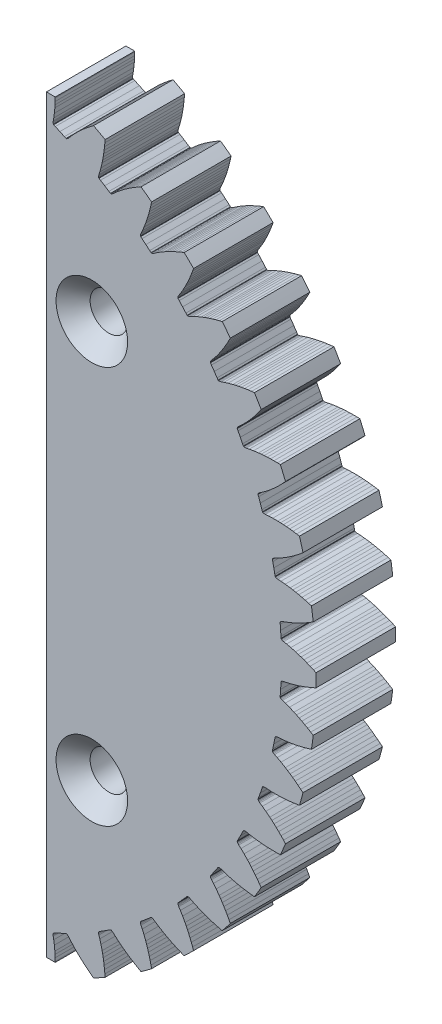
SolidWorks part; units mm, degrees
ref_plane "Front Plane" through (0, 0, 0) normal (0, 0, 1) x (1, 0, 0)
ref_plane "Top Plane" through (0, 0, 0) normal (0, 1, 0) x (1, 0, 0)
ref_plane "Right Plane" through (0, 0, 0) normal (1, 0, 0) x (0, 0, -1)
sketch "Model" plane through (0, 0, 0) normal (0, 0, 1) x (1, 0, 0)
  line L0 (12.0842, -6.6017) -> (12.3432, -6.4222)
  line L1 (12.3432, -6.4222) -> (12.5932, -6.2567)
  line L2 (12.5932, -6.2567) -> (12.8347, -6.1039)
  line L3 (12.8347, -6.1039) -> (13.0665, -5.964)
  line L4 (13.0665, -5.964) -> (13.2894, -5.8357)
  line L5 (13.2894, -5.8357) -> (13.5014, -5.7196)
  line L6 (13.5014, -5.7196) -> (13.8938, -5.5202)
  line L7 (13.8938, -5.5202) -> (14.2426, -5.361)
  line L8 (14.2426, -5.361) -> (14.4814, -5.2618)
  line L9 (14.4814, -5.2618) -> (14.5544, -5.2257)
  line L10 (14.5544, -5.2257) -> (14.6112, -5.1891)
  line L11 (14.6112, -5.1891) -> (14.6518, -5.1528)
  line L12 (14.6518, -5.1528) -> (14.6763, -5.1174)
  line L13 (14.6763, -5.1174) -> (14.6847, -5.0835)
  line L14 (14.6847, -5.0835) -> (14.6623, -4.9288)
  line L15 (14.6623, -4.9288) -> (14.6007, -4.4918)
  line L16 (14.6007, -4.4918) -> (14.5446, -4.054)
  line L17 (14.5446, -4.054) -> (14.5254, -3.8988)
  line L18 (14.5254, -3.8988) -> (14.5083, -3.8684)
  line L19 (14.5083, -3.8684) -> (14.4754, -3.8407)
  line L20 (14.4754, -3.8407) -> (14.4266, -3.8164)
  line L21 (14.4266, -3.8164) -> (14.3621, -3.7962)
  line L22 (14.3621, -3.7962) -> (14.2822, -3.7806)
  line L23 (14.2822, -3.7806) -> (14.0257, -3.748)
  line L24 (14.0257, -3.748) -> (13.6472, -3.6866)
  line L25 (13.6472, -3.6866) -> (13.216, -3.598)
  line L26 (13.216, -3.598) -> (12.981, -3.542)
  line L27 (12.981, -3.542) -> (12.7321, -3.4772)
  line L28 (12.7321, -3.4772) -> (12.4715, -3.4035)
  line L29 (12.4715, -3.4035) -> (12.1983, -3.32)
  line L30 (12.1983, -3.32) -> (11.9134, -3.2263)
  line L31 (11.9134, -3.2263) -> (11.6162, -3.1217)
  line L32 (11.6162, -3.1217) -> (11.3753, -3.0317)
  line L33 (11.298, -1.877) -> (11.5247, -1.7557)
  line L34 (11.5247, -1.7557) -> (11.8054, -1.6123)
  line L35 (11.8054, -1.6123) -> (12.0752, -1.4816)
  line L36 (12.0752, -1.4816) -> (12.3349, -1.3624)
  line L37 (12.3349, -1.3624) -> (12.5833, -1.2546)
  line L38 (12.5833, -1.2546) -> (12.8213, -1.1572)
  line L39 (12.8213, -1.1572) -> (13.0468, -1.0704)
  line L40 (13.0468, -1.0704) -> (13.4624, -0.9251)
  line L41 (13.4624, -0.9251) -> (13.8292, -0.8137)
  line L42 (13.8292, -0.8137) -> (14.0791, -0.7473)
  line L43 (14.0791, -0.7473) -> (14.1563, -0.7212)
  line L44 (14.1563, -0.7212) -> (14.2175, -0.6925)
  line L45 (14.2175, -0.6925) -> (14.2626, -0.662)
  line L46 (14.2626, -0.662) -> (14.2916, -0.6301)
  line L47 (14.2916, -0.6301) -> (14.3044, -0.5977)
  line L48 (14.3044, -0.5977) -> (14.3028, -0.4414)
  line L49 (14.3028, -0.4414) -> (14.3, 0)
  line L50 (14.3, 0) -> (14.3028, 0.4414)
  line L51 (14.3028, 0.4414) -> (14.3044, 0.5977)
  line L52 (14.3044, 0.5977) -> (14.2916, 0.6301)
  line L53 (14.2916, 0.6301) -> (14.2626, 0.662)
  line L54 (14.2626, 0.662) -> (14.2175, 0.6925)
  line L55 (14.2175, 0.6925) -> (14.1563, 0.7212)
  line L56 (14.1563, 0.7212) -> (14.0791, 0.7473)
  line L57 (14.0791, 0.7473) -> (13.8292, 0.8137)
  line L58 (13.8292, 0.8137) -> (13.4624, 0.9251)
  line L59 (13.4624, 0.9251) -> (13.0468, 1.0704)
  line L60 (13.0468, 1.0704) -> (12.8213, 1.1572)
  line L61 (12.8213, 1.1572) -> (12.5833, 1.2546)
  line L62 (12.5833, 1.2546) -> (12.3349, 1.3624)
  line L63 (12.3349, 1.3624) -> (12.0752, 1.4816)
  line L64 (12.0752, 1.4816) -> (11.8054, 1.6123)
  line L65 (11.8054, 1.6123) -> (11.5247, 1.7557)
  line L66 (11.5247, 1.7557) -> (11.298, 1.877)
  line L67 (11.3753, 3.0317) -> (11.6162, 3.1217)
  line L68 (11.6162, 3.1217) -> (11.9134, 3.2263)
  line L69 (11.9134, 3.2263) -> (12.1983, 3.32)
  line L70 (12.1983, 3.32) -> (12.4715, 3.4035)
  line L71 (12.4715, 3.4035) -> (12.7321, 3.4772)
  line L72 (12.7321, 3.4772) -> (12.981, 3.542)
  line L73 (12.981, 3.542) -> (13.216, 3.598)
  line L74 (13.216, 3.598) -> (13.6472, 3.6866)
  line L75 (13.6472, 3.6866) -> (14.0257, 3.748)
  line L76 (14.0257, 3.748) -> (14.2822, 3.7806)
  line L77 (14.2822, 3.7806) -> (14.3621, 3.7962)
  line L78 (14.3621, 3.7962) -> (14.4266, 3.8164)
  line L79 (14.4266, 3.8164) -> (14.4754, 3.8407)
  line L80 (14.4754, 3.8407) -> (14.5083, 3.8684)
  line L81 (14.5083, 3.8684) -> (14.5254, 3.8988)
  line L82 (14.5254, 3.8988) -> (14.5446, 4.054)
  line L83 (14.5446, 4.054) -> (14.6007, 4.4918)
  line L84 (14.6007, 4.4918) -> (14.6623, 4.9288)
  line L85 (14.6623, 4.9288) -> (14.6847, 5.0835)
  line L86 (14.6847, 5.0835) -> (14.6763, 5.1174)
  line L87 (14.6763, 5.1174) -> (14.6518, 5.1528)
  line L88 (14.6518, 5.1528) -> (14.6112, 5.1891)
  line L89 (14.6112, 5.1891) -> (14.5544, 5.2257)
  line L90 (14.5544, 5.2257) -> (14.4814, 5.2618)
  line L91 (14.4814, 5.2618) -> (14.2426, 5.361)
  line L92 (14.2426, 5.361) -> (13.8938, 5.5202)
  line L93 (13.8938, 5.5202) -> (13.5014, 5.7196)
  line L94 (13.5014, 5.7196) -> (13.2894, 5.8357)
  line L95 (13.2894, 5.8357) -> (13.0665, 5.964)
  line L96 (13.0665, 5.964) -> (12.8347, 6.1039)
  line L97 (12.8347, 6.1039) -> (12.5932, 6.2567)
  line L98 (12.5932, 6.2567) -> (12.3432, 6.4222)
  line L99 (12.3432, 6.4222) -> (12.0842, 6.6017)
  line L100 (12.0842, 6.6017) -> (11.8756, 6.7521)
  line L101 (12.1061, 7.8862) -> (12.3569, 7.9433)
  line L102 (12.3569, 7.9433) -> (12.6654, 8.0074)
  line L103 (12.6654, 8.0074) -> (12.9602, 8.0622)
  line L104 (12.9602, 8.0622) -> (13.2422, 8.1086)
  line L105 (13.2422, 8.1086) -> (13.5102, 8.1469)
  line L106 (13.5102, 8.1469) -> (13.7655, 8.178)
  line L107 (13.7655, 8.178) -> (14.006, 8.2021)
  line L108 (14.006, 8.2021) -> (14.4451, 8.2325)
  line L109 (14.4451, 8.2325) -> (14.8284, 8.2429)
  line L110 (14.8284, 8.2429) -> (15.0869, 8.241)
  line L111 (15.0869, 8.241) -> (15.1682, 8.2458)
  line L112 (15.1682, 8.2458) -> (15.2348, 8.2573)
  line L113 (15.2348, 8.2573) -> (15.2864, 8.2748)
  line L114 (15.2864, 8.2748) -> (15.3228, 8.2979)
  line L115 (15.3228, 8.2979) -> (15.3437, 8.3258)
  line L116 (15.3437, 8.3258) -> (15.3835, 8.477)
  line L117 (15.3835, 8.477) -> (15.4974, 8.9034)
  line L118 (15.4974, 8.9034) -> (15.6167, 9.3283)
  line L119 (15.6167, 9.3283) -> (15.6595, 9.4787)
  line L120 (15.6595, 9.4787) -> (15.6557, 9.5134)
  line L121 (15.6557, 9.5134) -> (15.6362, 9.5517)
  line L122 (15.6362, 9.5517) -> (15.6007, 9.5931)
  line L123 (15.6007, 9.5931) -> (15.5493, 9.6369)
  line L124 (15.5493, 9.6369) -> (15.4818, 9.6824)
  line L125 (15.4818, 9.6824) -> (15.2583, 9.8126)
  line L126 (15.2583, 9.8126) -> (14.9339, 10.0169)
  line L127 (14.9339, 10.0169) -> (14.5715, 10.2668)
  line L128 (14.5715, 10.2668) -> (14.377, 10.4101)
  line L129 (14.377, 10.4101) -> (14.1732, 10.5669)
  line L130 (14.1732, 10.5669) -> (13.962, 10.7365)
  line L131 (13.962, 10.7365) -> (13.7431, 10.9201)
  line L132 (13.7431, 10.9201) -> (13.5174, 11.1175)
  line L133 (13.5174, 11.1175) -> (13.2846, 11.3299)
  line L134 (13.2846, 11.3299) -> (13.0979, 11.5068)
  line L135 (13.4775, 12.6001) -> (13.7337, 12.6232)
  line L136 (13.7337, 12.6232) -> (14.048, 12.6456)
  line L137 (14.048, 12.6456) -> (14.3475, 12.6606)
  line L138 (14.3475, 12.6606) -> (14.633, 12.669)
  line L139 (14.633, 12.669) -> (14.9038, 12.6712)
  line L140 (14.9038, 12.6712) -> (15.161, 12.668)
  line L141 (15.161, 12.668) -> (15.4025, 12.6599)
  line L142 (15.4025, 12.6599) -> (15.8418, 12.6315)
  line L143 (15.8418, 12.6315) -> (16.223, 12.5907)
  line L144 (16.223, 12.5907) -> (16.479, 12.5544)
  line L145 (16.479, 12.5544) -> (16.5602, 12.5483)
  line L146 (16.5602, 12.5483) -> (16.6277, 12.5508)
  line L147 (16.6277, 12.5508) -> (16.6812, 12.5613)
  line L148 (16.6812, 12.5613) -> (16.7203, 12.5793)
  line L149 (16.7203, 12.5793) -> (16.7448, 12.6041)
  line L150 (16.7448, 12.6041) -> (16.8043, 12.7487)
  line L151 (16.8043, 12.7487) -> (16.9741, 13.1561)
  line L152 (16.9741, 13.1561) -> (17.149, 13.5614)
  line L153 (17.149, 13.5614) -> (17.2115, 13.7047)
  line L154 (17.2115, 13.7047) -> (17.2123, 13.7395)
  line L155 (17.2123, 13.7395) -> (17.1981, 13.7802)
  line L156 (17.1981, 13.7802) -> (17.1685, 13.8259)
  line L157 (17.1685, 13.8259) -> (17.1233, 13.8762)
  line L158 (17.1233, 13.8762) -> (17.0625, 13.9303)
  line L159 (17.0625, 13.9303) -> (16.8584, 14.0891)
  line L160 (16.8584, 14.0891) -> (16.5641, 14.3348)
  line L161 (16.5641, 14.3348) -> (16.2382, 14.6308)
  line L162 (16.2382, 14.6308) -> (16.0645, 14.7988)
  line L163 (16.0645, 14.7988) -> (15.8834, 14.9813)
  line L164 (15.8834, 14.9813) -> (15.6968, 15.1776)
  line L165 (15.6968, 15.1776) -> (15.5043, 15.3887)
  line L166 (15.5043, 15.3887) -> (15.3069, 15.6144)
  line L167 (15.3069, 15.6144) -> (15.1044, 15.8559)
  line L168 (15.1044, 15.8559) -> (14.943, 16.0561)
  line L169 (15.465, 17.089) -> (15.7219, 17.0778)
  line L170 (15.7219, 17.0778) -> (16.0364, 17.0581)
  line L171 (16.0364, 17.0581) -> (16.3352, 17.0331)
  line L172 (16.3352, 17.0331) -> (16.6194, 17.0033)
  line L173 (16.6194, 17.0033) -> (16.8881, 16.9695)
  line L174 (16.8881, 16.9695) -> (17.1425, 16.932)
  line L175 (17.1425, 16.932) -> (17.3808, 16.8918)
  line L176 (17.3808, 16.8918) -> (17.8123, 16.805)
  line L177 (17.8123, 16.805) -> (18.1847, 16.7138)
  line L178 (18.1847, 16.7138) -> (18.4336, 16.6437)
  line L179 (18.4336, 16.6437) -> (18.5133, 16.6268)
  line L180 (18.5133, 16.6268) -> (18.5805, 16.6203)
  line L181 (18.5805, 16.6203) -> (18.6349, 16.6236)
  line L182 (18.6349, 16.6236) -> (18.6761, 16.6362)
  line L183 (18.6761, 16.6362) -> (18.7037, 16.6576)
  line L184 (18.7037, 16.6576) -> (18.7819, 16.7929)
  line L185 (18.7819, 16.7929) -> (19.0045, 17.1741)
  line L186 (19.0045, 17.1741) -> (19.2318, 17.5524)
  line L187 (19.2318, 17.5524) -> (19.3129, 17.6861)
  line L188 (19.3129, 17.6861) -> (19.3183, 17.7206)
  line L189 (19.3183, 17.7206) -> (19.3096, 17.7627)
  line L190 (19.3096, 17.7627) -> (19.2864, 17.812)
  line L191 (19.2864, 17.812) -> (19.2483, 17.8678)
  line L192 (19.2483, 17.8678) -> (19.1952, 17.9296)
  line L193 (19.1952, 17.9296) -> (19.0141, 18.1141)
  line L194 (19.0141, 18.1141) -> (18.7552, 18.3969)
  line L195 (18.7552, 18.3969) -> (18.4717, 18.7337)
  line L196 (18.4717, 18.7337) -> (18.3219, 18.9233)
  line L197 (18.3219, 18.9233) -> (18.1668, 19.1284)
  line L198 (18.1668, 19.1284) -> (18.008, 19.3477)
  line L199 (18.008, 19.3477) -> (17.8453, 19.5826)
  line L200 (17.8453, 19.5826) -> (17.6798, 19.8326)
  line L201 (17.6798, 19.8326) -> (17.5113, 20.099)
  line L202 (17.5113, 20.099) -> (17.378, 20.3189)
  line L203 (18.033, 21.273) -> (18.2862, 21.2277)
  line L204 (18.2862, 21.2277) -> (18.5952, 21.1662)
  line L205 (18.5952, 21.1662) -> (18.8881, 21.1016)
  line L206 (18.8881, 21.1016) -> (19.1657, 21.0343)
  line L207 (19.1657, 21.0343) -> (19.4275, 20.9649)
  line L208 (19.4275, 20.9649) -> (19.6746, 20.8938)
  line L209 (19.6746, 20.8938) -> (19.9054, 20.8222)
  line L210 (19.9054, 20.8222) -> (20.3216, 20.6787)
  line L211 (20.3216, 20.6787) -> (20.6785, 20.5387)
  line L212 (20.6785, 20.5387) -> (20.9158, 20.436)
  line L213 (20.9158, 20.436) -> (20.9925, 20.4086)
  line L214 (20.9925, 20.4086) -> (21.0583, 20.3932)
  line L215 (21.0583, 20.3932) -> (21.1126, 20.3893)
  line L216 (21.1126, 20.3893) -> (21.1551, 20.3963)
  line L217 (21.1551, 20.3963) -> (21.1853, 20.4138)
  line L218 (21.1853, 20.4138) -> (21.2809, 20.5375)
  line L219 (21.2809, 20.5375) -> (21.5523, 20.8856)
  line L220 (21.5523, 20.8856) -> (21.828, 21.2302)
  line L221 (21.828, 21.2302) -> (21.9261, 21.3519)
  line L222 (21.9261, 21.3519) -> (21.9362, 21.3853)
  line L223 (21.9362, 21.3853) -> (21.9331, 21.4283)
  line L224 (21.9331, 21.4283) -> (21.9167, 21.4802)
  line L225 (21.9167, 21.4802) -> (21.8864, 21.5406)
  line L226 (21.8864, 21.5406) -> (21.842, 21.6089)
  line L227 (21.842, 21.6089) -> (21.6871, 21.816)
  line L228 (21.6871, 21.816) -> (21.4682, 22.1307)
  line L229 (21.4682, 22.1307) -> (21.2321, 22.5023)
  line L230 (21.2321, 22.5023) -> (21.109, 22.7102)
  line L231 (21.109, 22.7102) -> (20.9825, 22.9341)
  line L232 (20.9825, 22.9341) -> (20.8544, 23.1727)
  line L233 (20.8544, 23.1727) -> (20.7245, 23.4271)
  line L234 (20.7245, 23.4271) -> (20.5937, 23.697)
  line L235 (20.5937, 23.697) -> (20.4623, 23.9834)
  line L236 (20.4623, 23.9834) -> (20.3595, 24.2191)
  line L237 (21.1358, 25.0774) -> (21.3807, 24.9988)
  line L238 (21.3807, 24.9988) -> (21.6788, 24.8967)
  line L239 (21.6788, 24.8967) -> (21.9604, 24.7936)
  line L240 (21.9604, 24.7936) -> (22.2266, 24.6898)
  line L241 (22.2266, 24.6898) -> (22.4767, 24.5862)
  line L242 (22.4767, 24.5862) -> (22.7122, 24.4828)
  line L243 (22.7122, 24.4828) -> (22.9314, 24.381)
  line L244 (22.9314, 24.381) -> (23.3247, 24.1834)
  line L245 (23.3247, 24.1834) -> (23.6598, 23.9971)
  line L246 (23.6598, 23.9971) -> (23.8813, 23.8636)
  line L247 (23.8813, 23.8636) -> (23.9537, 23.8263)
  line L248 (23.9537, 23.8263) -> (24.0168, 23.8022)
  line L249 (24.0168, 23.8022) -> (24.0702, 23.7911)
  line L250 (24.0702, 23.7911) -> (24.1132, 23.7924)
  line L251 (24.1132, 23.7924) -> (24.1454, 23.8057)
  line L252 (24.1454, 23.8057) -> (24.2567, 23.9155)
  line L253 (24.2567, 23.9155) -> (24.572, 24.2244)
  line L254 (24.572, 24.2244) -> (24.8912, 24.5292)
  line L255 (24.8912, 24.5292) -> (25.0047, 24.6367)
  line L256 (25.0047, 24.6367) -> (25.0191, 24.6685)
  line L257 (25.0191, 24.6685) -> (25.0218, 24.7115)
  line L258 (25.0218, 24.7115) -> (25.0124, 24.7651)
  line L259 (25.0124, 24.7651) -> (24.9905, 24.829)
  line L260 (24.9905, 24.829) -> (24.9556, 24.9026)
  line L261 (24.9556, 24.9026) -> (24.8297, 25.1285)
  line L262 (24.8297, 25.1285) -> (24.6546, 25.4696)
  line L263 (24.6546, 25.4696) -> (24.4702, 25.8693)
  line L264 (24.4702, 25.8693) -> (24.3759, 26.0917)
  line L265 (24.3759, 26.0917) -> (24.2804, 26.3305)
  line L266 (24.2804, 26.3305) -> (24.1852, 26.5841)
  line L267 (24.1852, 26.5841) -> (24.0904, 26.8536)
  line L268 (24.0904, 26.8536) -> (23.9968, 27.1384)
  line L269 (23.9968, 27.1384) -> (23.9047, 27.4398)
  line L270 (23.9047, 27.4398) -> (23.8342, 27.6871)
  line L271 (24.718, 28.4343) -> (24.9502, 28.3237)
  line L272 (24.9502, 28.3237) -> (25.232, 28.1828)
  line L273 (25.232, 28.1828) -> (25.4974, 28.0431)
  line L274 (25.4974, 28.0431) -> (25.7474, 27.9048)
  line L275 (25.7474, 27.9048) -> (25.9815, 27.7687)
  line L276 (25.9815, 27.7687) -> (26.2011, 27.6349)
  line L277 (26.2011, 27.6349) -> (26.4048, 27.5048)
  line L278 (26.4048, 27.5048) -> (26.7682, 27.2565)
  line L279 (26.7682, 27.2565) -> (27.0755, 27.0272)
  line L280 (27.0755, 27.0272) -> (27.2772, 26.8654)
  line L281 (27.2772, 26.8654) -> (27.344, 26.8188)
  line L282 (27.344, 26.8188) -> (27.4033, 26.7865)
  line L283 (27.4033, 26.7865) -> (27.4547, 26.7683)
  line L284 (27.4547, 26.7683) -> (27.4975, 26.7639)
  line L285 (27.4975, 26.7639) -> (27.5313, 26.7728)
  line L286 (27.5313, 26.7728) -> (27.6562, 26.8668)
  line L287 (27.6562, 26.8668) -> (28.0098, 27.1309)
  line L288 (28.0098, 27.1309) -> (28.3668, 27.3904)
  line L289 (28.3668, 27.3904) -> (28.4936, 27.4818)
  line L290 (28.4936, 27.4818) -> (28.5121, 27.5114)
  line L291 (28.5121, 27.5114) -> (28.5206, 27.5537)
  line L292 (28.5206, 27.5537) -> (28.5184, 27.6081)
  line L293 (28.5184, 27.6081) -> (28.5052, 27.6744)
  line L294 (28.5052, 27.6744) -> (28.4804, 27.7519)
  line L295 (28.4804, 27.7519) -> (28.3857, 27.9926)
  line L296 (28.3857, 27.9926) -> (28.2577, 28.3539)
  line L297 (28.2577, 28.3539) -> (28.1282, 28.7747)
  line L298 (28.1282, 28.7747) -> (28.0643, 29.0077)
  line L299 (28.0643, 29.0077) -> (28.0016, 29.2571)
  line L300 (28.0016, 29.2571) -> (27.941, 29.5211)
  line L301 (27.941, 29.5211) -> (27.8829, 29.8008)
  line L302 (27.8829, 29.8008) -> (27.8281, 30.0956)
  line L303 (27.8281, 30.0956) -> (27.777, 30.4066)
  line L304 (27.777, 30.4066) -> (27.7402, 30.6611)
  line L305 (28.7157, 31.2838) -> (28.931, 31.1432)
  line L306 (28.931, 31.1432) -> (29.1916, 30.966)
  line L307 (29.1916, 30.966) -> (29.4359, 30.7922)
  line L308 (29.4359, 30.7922) -> (29.6652, 30.6218)
  line L309 (29.6652, 30.6218) -> (29.8792, 30.4557)
  line L310 (29.8792, 30.4557) -> (30.079, 30.2938)
  line L311 (30.079, 30.2938) -> (30.2635, 30.1378)
  line L312 (30.2635, 30.1378) -> (30.5906, 29.8432)
  line L313 (30.5906, 29.8432) -> (30.8645, 29.575)
  line L314 (30.8645, 29.575) -> (31.0429, 29.3878)
  line L315 (31.0429, 29.3878) -> (31.1029, 29.3326)
  line L316 (31.1029, 29.3326) -> (31.1574, 29.2928)
  line L317 (31.1574, 29.2928) -> (31.2059, 29.2679)
  line L318 (31.2059, 29.2679) -> (31.2477, 29.2578)
  line L319 (31.2477, 29.2578) -> (31.2824, 29.2621)
  line L320 (31.2824, 29.2621) -> (31.4187, 29.3387)
  line L321 (31.4187, 29.3387) -> (31.8044, 29.5532)
  line L322 (31.8044, 29.5532) -> (32.1928, 29.7629)
  line L323 (32.1928, 29.7629) -> (32.3307, 29.8366)
  line L324 (32.3307, 29.8366) -> (32.3529, 29.8635)
  line L325 (32.3529, 29.8635) -> (32.3669, 29.9042)
  line L326 (32.3669, 29.9042) -> (32.3721, 29.9584)
  line L327 (32.3721, 29.9584) -> (32.3678, 30.0258)
  line L328 (32.3678, 30.0258) -> (32.3536, 30.106)
  line L329 (32.3536, 30.106) -> (32.2918, 30.3571)
  line L330 (32.2918, 30.3571) -> (32.2131, 30.7323)
  line L331 (32.2131, 30.7323) -> (32.1408, 31.1666)
  line L332 (32.1408, 31.1666) -> (32.1086, 31.4061)
  line L333 (32.1086, 31.4061) -> (32.0796, 31.6616)
  line L334 (32.0796, 31.6616) -> (32.0547, 31.9313)
  line L335 (32.0547, 31.9313) -> (32.0345, 32.2162)
  line L336 (32.0345, 32.2162) -> (32.0195, 32.5157)
  line L337 (32.0195, 32.5157) -> (32.0103, 32.8307)
  line L338 (32.0103, 32.8307) -> (32.0077, 33.0879)
  line L339 (33.0575, 33.575) -> (33.2521, 33.407)
  line L340 (33.2521, 33.407) -> (33.4868, 33.1966)
  line L341 (33.4868, 33.1966) -> (33.7058, 32.9918)
  line L342 (33.7058, 32.9918) -> (33.9103, 32.7923)
  line L343 (33.9103, 32.7923) -> (34.1002, 32.5993)
  line L344 (34.1002, 32.5993) -> (34.2766, 32.4122)
  line L345 (34.2766, 32.4122) -> (34.4387, 32.2329)
  line L346 (34.4387, 32.2329) -> (34.7237, 31.8974)
  line L347 (34.7237, 31.8974) -> (34.9594, 31.595)
  line L348 (34.9594, 31.595) -> (35.1112, 31.3857)
  line L349 (35.1112, 31.3857) -> (35.1633, 31.3231)
  line L350 (35.1633, 31.3231) -> (35.212, 31.2763)
  line L351 (35.212, 31.2763) -> (35.2568, 31.2452)
  line L352 (35.2568, 31.2452) -> (35.2969, 31.2296)
  line L353 (35.2969, 31.2296) -> (35.3318, 31.2293)
  line L354 (35.3318, 31.2293) -> (35.4771, 31.287)
  line L355 (35.4771, 31.287) -> (35.888, 31.4482)
  line L356 (35.888, 31.4482) -> (36.3008, 31.6042)
  line L357 (36.3008, 31.6042) -> (36.4473, 31.6589)
  line L358 (36.4473, 31.6589) -> (36.4729, 31.6825)
  line L359 (36.4729, 31.6825) -> (36.4922, 31.721)
  line L360 (36.4922, 31.721) -> (36.5046, 31.7741)
  line L361 (36.5046, 31.7741) -> (36.5093, 31.8415)
  line L362 (36.5093, 31.8415) -> (36.5059, 31.9229)
  line L363 (36.5059, 31.9229) -> (36.4781, 32.18)
  line L364 (36.4781, 32.18) -> (36.4501, 32.5623)
  line L365 (36.4501, 32.5623) -> (36.4364, 33.0023)
  line L366 (36.4364, 33.0023) -> (36.4364, 33.244)
  line L367 (36.4364, 33.244) -> (36.4417, 33.5011)
  line L368 (36.4417, 33.5011) -> (36.453, 33.7717)
  line L369 (36.453, 33.7717) -> (36.4709, 34.0568)
  line L370 (36.4709, 34.0568) -> (36.496, 34.3556)
  line L371 (36.496, 34.3556) -> (36.5289, 34.669)
  line L372 (36.5289, 34.669) -> (36.5605, 34.9242)
  line L373 (37.6659, 35.2671) -> (37.8365, 35.0746)
  line L374 (37.8365, 35.0746) -> (38.0409, 34.8349)
  line L375 (38.0409, 34.8349) -> (38.2307, 34.6027)
  line L376 (38.2307, 34.6027) -> (38.4068, 34.3777)
  line L377 (38.4068, 34.3777) -> (38.5693, 34.1611)
  line L378 (38.5693, 34.1611) -> (38.7192, 33.9521)
  line L379 (38.7192, 33.9521) -> (38.8559, 33.7529)
  line L380 (38.8559, 33.7529) -> (39.0936, 33.3823)
  line L381 (39.0936, 33.3823) -> (39.287, 33.0513)
  line L382 (39.287, 33.0513) -> (39.4096, 32.8236)
  line L383 (39.4096, 32.8236) -> (39.4528, 32.7546)
  line L384 (39.4528, 32.7546) -> (39.4949, 32.7017)
  line L385 (39.4949, 32.7017) -> (39.5351, 32.6649)
  line L386 (39.5351, 32.6649) -> (39.5727, 32.6441)
  line L387 (39.5727, 32.6441) -> (39.6073, 32.6391)
  line L388 (39.6073, 32.6391) -> (39.759, 32.677)
  line L389 (39.759, 32.677) -> (40.1877, 32.782)
  line L390 (40.1877, 32.782) -> (40.6176, 32.8816)
  line L391 (40.6176, 32.8816) -> (40.7701, 32.9162)
  line L392 (40.7701, 32.9162) -> (40.7987, 32.9363)
  line L393 (40.7987, 32.9363) -> (40.8229, 32.9718)
  line L394 (40.8229, 32.9718) -> (40.8422, 33.0228)
  line L395 (40.8422, 33.0228) -> (40.8559, 33.0889)
  line L396 (40.8559, 33.0889) -> (40.8634, 33.1701)
  line L397 (40.8634, 33.1701) -> (40.8701, 33.4286)
  line L398 (40.8701, 33.4286) -> (40.8933, 33.8112)
  line L399 (40.8933, 33.8112) -> (40.9384, 34.2491)
  line L400 (40.9384, 34.2491) -> (40.9705, 34.4886)
  line L401 (40.9705, 34.4886) -> (41.0101, 34.7427)
  line L402 (41.0101, 34.7427) -> (41.0574, 35.0094)
  line L403 (41.0574, 35.0094) -> (41.1131, 35.2896)
  line L404 (41.1131, 35.2896) -> (41.1778, 35.5824)
  line L405 (41.1778, 35.5824) -> (41.2521, 35.8886)
  line L406 (41.2521, 35.8886) -> (41.3176, 36.1373)
  line L407 (42.4587, 36.3298) -> (42.6021, 36.1163)
  line L408 (42.6021, 36.1163) -> (42.7728, 35.8515)
  line L409 (42.7728, 35.8515) -> (42.93, 35.5961)
  line L410 (42.93, 35.5961) -> (43.0745, 35.3496)
  line L411 (43.0745, 35.3496) -> (43.2066, 35.1132)
  line L412 (43.2066, 35.1132) -> (43.3274, 34.8862)
  line L413 (43.3274, 34.8862) -> (43.4363, 34.6705)
  line L414 (43.4363, 34.6705) -> (43.6225, 34.2716)
  line L415 (43.6225, 34.2716) -> (43.77, 33.9177)
  line L416 (43.77, 33.9177) -> (43.8612, 33.6757)
  line L417 (43.8612, 33.6757) -> (43.8948, 33.6016)
  line L418 (43.8948, 33.6016) -> (43.9295, 33.5436)
  line L419 (43.9295, 33.5436) -> (43.9644, 33.5017)
  line L420 (43.9644, 33.5017) -> (43.999, 33.4761)
  line L421 (43.999, 33.4761) -> (44.0325, 33.4665)
  line L422 (44.0325, 33.4665) -> (44.1879, 33.4838)
  line L423 (44.1879, 33.4838) -> (44.6268, 33.5308)
  line L424 (44.6268, 33.5308) -> (45.0662, 33.5722)
  line L425 (45.0662, 33.5722) -> (45.2219, 33.5862)
  line L426 (45.2219, 33.5862) -> (45.2529, 33.6022)
  line L427 (45.2529, 33.6022) -> (45.2817, 33.6343)
  line L428 (45.2817, 33.6343) -> (45.3076, 33.6822)
  line L429 (45.3076, 33.6822) -> (45.33, 33.7459)
  line L430 (45.33, 33.7459) -> (45.3482, 33.8253)
  line L431 (45.3482, 33.8253) -> (45.3893, 34.0806)
  line L432 (45.3893, 34.0806) -> (45.4633, 34.4568)
  line L433 (45.4633, 34.4568) -> (45.5663, 34.8848)
  line L434 (45.5663, 34.8848) -> (45.6302, 35.1178)
  line L435 (45.6302, 35.1178) -> (45.7032, 35.3644)
  line L436 (45.7032, 35.3644) -> (45.7856, 35.6224)
  line L437 (45.7856, 35.6224) -> (45.8782, 35.8926)
  line L438 (45.8782, 35.8926) -> (45.9813, 36.1742)
  line L439 (45.9813, 36.1742) -> (46.0958, 36.4678)
  line L440 (46.0958, 36.4678) -> (46.1938, 36.7056)
  line L441 (47.3505, 36.7443) -> (47.4641, 36.5136)
  line L442 (47.4641, 36.5136) -> (47.598, 36.2283)
  line L443 (47.598, 36.2283) -> (47.7197, 35.9542)
  line L444 (47.7197, 35.9542) -> (47.8301, 35.6907)
  line L445 (47.8301, 35.6907) -> (47.9295, 35.4388)
  line L446 (47.9295, 35.4388) -> (48.0189, 35.1977)
  line L447 (48.0189, 35.1977) -> (48.0982, 34.9694)
  line L448 (48.0982, 34.9694) -> (48.2295, 34.5493)
  line L449 (48.2295, 34.5493) -> (48.3285, 34.1789)
  line L450 (48.3285, 34.1789) -> (48.3866, 33.9269)
  line L451 (48.3866, 33.9269) -> (48.4101, 33.8489)
  line L452 (48.4101, 33.8489) -> (48.4367, 33.7868)
  line L453 (48.4367, 33.7868) -> (48.4657, 33.7407)
  line L454 (48.4657, 33.7407) -> (48.4966, 33.7107)
  line L455 (48.4966, 33.7107) -> (48.5286, 33.6967)
  line L456 (48.5286, 33.6967) -> (48.6849, 33.6932)
  line L457 (48.6849, 33.6932) -> (49.1261, 33.6812)
  line L458 (49.1261, 33.6812) -> (49.5671, 33.6637)
  line L459 (49.5671, 33.6637) -> (49.7233, 33.6568)
  line L460 (49.7233, 33.6568) -> (49.7561, 33.6686)
  line L461 (49.7561, 33.6686) -> (49.7889, 33.6965)
  line L462 (49.7889, 33.6965) -> (49.821, 33.7405)
  line L463 (49.821, 33.7405) -> (49.8517, 33.8007)
  line L464 (49.8517, 33.8007) -> (49.8803, 33.877)
  line L465 (49.8803, 33.877) -> (49.9551, 34.1245)
  line L466 (49.9551, 34.1245) -> (50.0786, 34.4874)
  line L467 (50.0786, 34.4874) -> (50.2377, 34.8979)
  line L468 (50.2377, 34.8979) -> (50.332, 35.1204)
  line L469 (50.332, 35.1204) -> (50.4373, 35.355)
  line L470 (50.4373, 35.355) -> (50.5534, 35.5997)
  line L471 (50.5534, 35.5997) -> (50.6812, 35.8552)
  line L472 (50.6812, 35.8552) -> (50.8209, 36.1205)
  line L473 (50.8209, 36.1205) -> (50.9735, 36.3962)
  line L474 (50.9735, 36.3962) -> (51.1023, 36.6188)
  line L475 (52.2538, 36.503) -> (52.3357, 36.2592)
  line L476 (52.3357, 36.2592) -> (52.4303, 35.9586)
  line L477 (52.4303, 35.9586) -> (52.5144, 35.6708)
  line L478 (52.5144, 35.6708) -> (52.5887, 35.3949)
  line L479 (52.5887, 35.3949) -> (52.6537, 35.132)
  line L480 (52.6537, 35.132) -> (52.7102, 34.8811)
  line L481 (52.7102, 34.8811) -> (52.7583, 34.6443)
  line L482 (52.7583, 34.6443) -> (52.8325, 34.2104)
  line L483 (52.8325, 34.2104) -> (52.8812, 33.8301)
  line L484 (52.8812, 33.8301) -> (52.9052, 33.5727)
  line L485 (52.9052, 33.5727) -> (52.9181, 33.4922)
  line L486 (52.9181, 33.4922) -> (52.9361, 33.4271)
  line L487 (52.9361, 33.4271) -> (52.9588, 33.3776)
  line L488 (52.9588, 33.3776) -> (52.9854, 33.3437)
  line L489 (52.9854, 33.3437) -> (53.0152, 33.3256)
  line L490 (53.0152, 33.3256) -> (53.1696, 33.3012)
  line L491 (53.1696, 33.3012) -> (53.6053, 33.2306)
  line L492 (53.6053, 33.2306) -> (54.0401, 33.1544)
  line L493 (54.0401, 33.1544) -> (54.1939, 33.1268)
  line L494 (54.1939, 33.1268) -> (54.2281, 33.1341)
  line L495 (54.2281, 33.1341) -> (54.2643, 33.1574)
  line L496 (54.2643, 33.1574) -> (54.3019, 33.1968)
  line L497 (54.3019, 33.1968) -> (54.3403, 33.2523)
  line L498 (54.3403, 33.2523) -> (54.3789, 33.3241)
  line L499 (54.3789, 33.3241) -> (54.486, 33.5594)
  line L500 (54.486, 33.5594) -> (54.6568, 33.9027)
  line L501 (54.6568, 33.9027) -> (54.8692, 34.2882)
  line L502 (54.8692, 34.2882) -> (54.9923, 34.4962)
  line L503 (54.9923, 34.4962) -> (55.128, 34.7147)
  line L504 (55.128, 34.7147) -> (55.2756, 34.9417)
  line L505 (55.2756, 34.9417) -> (55.4363, 35.1779)
  line L506 (55.4363, 35.1779) -> (55.6101, 35.4223)
  line L507 (55.6101, 35.4223) -> (55.7981, 35.6752)
  line L508 (55.7981, 35.6752) -> (55.9554, 35.8786)
  line L509 (57.0812, 35.6103) -> (57.1299, 35.3578)
  line L510 (57.1299, 35.3578) -> (57.1836, 35.0473)
  line L511 (57.1836, 35.0473) -> (57.2286, 34.7508)
  line L512 (57.2286, 34.7508) -> (57.2655, 34.4675)
  line L513 (57.2655, 34.4675) -> (57.2948, 34.1983)
  line L514 (57.2948, 34.1983) -> (57.3173, 33.9421)
  line L515 (57.3173, 33.9421) -> (57.3334, 33.701)
  line L516 (57.3334, 33.701) -> (57.3491, 33.2611)
  line L517 (57.3491, 33.2611) -> (57.3468, 32.8777)
  line L518 (57.3468, 32.8777) -> (57.3362, 32.6193)
  line L519 (57.3362, 32.6193) -> (57.3383, 32.5379)
  line L520 (57.3383, 32.5379) -> (57.3475, 32.471)
  line L521 (57.3475, 32.471) -> (57.3633, 32.4188)
  line L522 (57.3633, 32.4188) -> (57.3852, 32.3817)
  line L523 (57.3852, 32.3817) -> (57.4123, 32.3598)
  line L524 (57.4123, 32.3598) -> (57.5621, 32.3151)
  line L525 (57.5621, 32.3151) -> (57.9845, 32.187)
  line L526 (57.9845, 32.187) -> (58.4052, 32.0535)
  line L527 (58.4052, 32.0535) -> (58.554, 32.0057)
  line L528 (58.554, 32.0057) -> (58.5888, 32.0083)
  line L529 (58.5888, 32.0083) -> (58.6278, 32.0266)
  line L530 (58.6278, 32.0266) -> (58.6704, 32.0606)
  line L531 (58.6704, 32.0606) -> (58.7159, 32.1105)
  line L532 (58.7159, 32.1105) -> (58.7636, 32.1765)
  line L533 (58.7636, 32.1765) -> (58.9012, 32.3955)
  line L534 (58.9012, 32.3955) -> (59.1162, 32.7129)
  line L535 (59.1162, 32.7129) -> (59.3781, 33.0667)
  line L536 (59.3781, 33.0667) -> (59.5278, 33.2564)
  line L537 (59.5278, 33.2564) -> (59.6914, 33.4549)
  line L538 (59.6914, 33.4549) -> (59.8679, 33.6602)
  line L539 (59.8679, 33.6602) -> (60.0587, 33.8729)
  line L540 (60.0587, 33.8729) -> (60.2635, 34.0919)
  line L541 (60.2635, 34.0919) -> (60.4836, 34.3175)
  line L542 (60.4836, 34.3175) -> (60.6666, 34.4981)
  line L543 (61.7466, 34.0822) -> (61.7612, 33.8254)
  line L544 (61.7612, 33.8254) -> (61.773, 33.5105)
  line L545 (61.773, 33.5105) -> (61.7781, 33.2107)
  line L546 (61.7781, 33.2107) -> (61.7769, 32.925)
  line L547 (61.7769, 32.925) -> (61.7701, 32.6543)
  line L548 (61.7701, 32.6543) -> (61.7582, 32.3974)
  line L549 (61.7582, 32.3974) -> (61.7421, 32.1563)
  line L550 (61.7421, 32.1563) -> (61.699, 31.7182)
  line L551 (61.699, 31.7182) -> (61.6455, 31.3385)
  line L552 (61.6455, 31.3385) -> (61.6006, 31.0839)
  line L553 (61.6006, 31.0839) -> (61.5918, 31.0029)
  line L554 (61.5918, 31.0029) -> (61.592, 30.9353)
  line L555 (61.592, 30.9353) -> (61.6008, 30.8816)
  line L556 (61.6008, 30.8816) -> (61.6175, 30.8419)
  line L557 (61.6175, 30.8419) -> (61.6415, 30.8166)
  line L558 (61.6415, 30.8166) -> (61.784, 30.7522)
  line L559 (61.784, 30.7522) -> (62.1855, 30.569)
  line L560 (62.1855, 30.569) -> (62.5847, 30.3807)
  line L561 (62.5847, 30.3807) -> (62.7258, 30.3134)
  line L562 (62.7258, 30.3134) -> (62.7606, 30.3114)
  line L563 (62.7606, 30.3114) -> (62.8017, 30.3243)
  line L564 (62.8017, 30.3243) -> (62.8484, 30.3523)
  line L565 (62.8484, 30.3523) -> (62.9002, 30.3957)
  line L566 (62.9002, 30.3957) -> (62.9563, 30.4548)
  line L567 (62.9563, 30.4548) -> (63.1218, 30.6535)
  line L568 (63.1218, 30.6535) -> (63.3772, 30.9394)
  line L569 (63.3772, 30.9394) -> (63.6839, 31.2551)
  line L570 (63.6839, 31.2551) -> (63.8576, 31.4232)
  line L571 (63.8576, 31.4232) -> (64.0462, 31.5981)
  line L572 (64.0462, 31.5981) -> (64.2485, 31.778)
  line L573 (64.2485, 31.778) -> (64.4659, 31.9634)
  line L574 (64.4659, 31.9634) -> (64.6981, 32.1531)
  line L575 (64.6981, 32.1531) -> (64.9463, 32.3474)
  line L576 (64.9463, 32.3474) -> (65.1517, 32.502)
  line L577 (66.1666, 31.9458) -> (66.1469, 31.6894)
  line L578 (66.1469, 31.6894) -> (66.1167, 31.3757)
  line L579 (66.1167, 31.3757) -> (66.0817, 31.0779)
  line L580 (66.0817, 31.0779) -> (66.0424, 30.7949)
  line L581 (66.0424, 30.7949) -> (65.9996, 30.5275)
  line L582 (65.9996, 30.5275) -> (65.9536, 30.2745)
  line L583 (65.9536, 30.2745) -> (65.9055, 30.0377)
  line L584 (65.9055, 30.0377) -> (65.8044, 29.6093)
  line L585 (65.8044, 29.6093) -> (65.7008, 29.2401)
  line L586 (65.7008, 29.2401) -> (65.6224, 28.9937)
  line L587 (65.6224, 28.9937) -> (65.6028, 28.9147)
  line L588 (65.6028, 28.9147) -> (65.5941, 28.8477)
  line L589 (65.5941, 28.8477) -> (65.5956, 28.7932)
  line L590 (65.5956, 28.7932) -> (65.6068, 28.7517)
  line L591 (65.6068, 28.7517) -> (65.6272, 28.7234)
  line L592 (65.6272, 28.7234) -> (65.7599, 28.6406)
  line L593 (65.7599, 28.6406) -> (66.1334, 28.4055)
  line L594 (66.1334, 28.4055) -> (66.5039, 28.1656)
  line L595 (66.5039, 28.1656) -> (66.6348, 28.0801)
  line L596 (66.6348, 28.0801) -> (66.6691, 28.0735)
  line L597 (66.6691, 28.0735) -> (66.7115, 28.0808)
  line L598 (66.7115, 28.0808) -> (66.7615, 28.1024)
  line L599 (66.7615, 28.1024) -> (66.8186, 28.1385)
  line L600 (66.8186, 28.1385) -> (66.8821, 28.1896)
  line L601 (66.8821, 28.1896) -> (67.0726, 28.3644)
  line L602 (67.0726, 28.3644) -> (67.3638, 28.6138)
  line L603 (67.3638, 28.6138) -> (67.7099, 28.8858)
  line L604 (67.7099, 28.8858) -> (67.9044, 29.0292)
  line L605 (67.9044, 29.0292) -> (68.1146, 29.1774)
  line L606 (68.1146, 29.1774) -> (68.3391, 29.3288)
  line L607 (68.3391, 29.3288) -> (68.5793, 29.4835)
  line L608 (68.5793, 29.4835) -> (68.8347, 29.6406)
  line L609 (68.8347, 29.6406) -> (69.1065, 29.8)
  line L610 (69.1065, 29.8) -> (69.3308, 29.9259)
  line L611 (70.2625, 29.2394) -> (70.2087, 28.9879)
  line L612 (70.2087, 28.9879) -> (70.137, 28.6811)
  line L613 (70.137, 28.6811) -> (70.0626, 28.3906)
  line L614 (70.0626, 28.3906) -> (69.986, 28.1153)
  line L615 (69.986, 28.1153) -> (69.9079, 27.856)
  line L616 (69.9079, 27.856) -> (69.8286, 27.6114)
  line L617 (69.8286, 27.6114) -> (69.7493, 27.3831)
  line L618 (69.7493, 27.3831) -> (69.592, 26.972)
  line L619 (69.592, 26.972) -> (69.4402, 26.62)
  line L620 (69.4402, 26.62) -> (69.3296, 26.3862)
  line L621 (69.3296, 26.3862) -> (69.2997, 26.3104)
  line L622 (69.2997, 26.3104) -> (69.2821, 26.2452)
  line L623 (69.2821, 26.2452) -> (69.2763, 26.1911)
  line L624 (69.2763, 26.1911) -> (69.2819, 26.1484)
  line L625 (69.2819, 26.1484) -> (69.2984, 26.1176)
  line L626 (69.2984, 26.1176) -> (69.4188, 26.0179)
  line L627 (69.4188, 26.0179) -> (69.7577, 25.7351)
  line L628 (69.7577, 25.7351) -> (70.0929, 25.448)
  line L629 (70.0929, 25.448) -> (70.2112, 25.3458)
  line L630 (70.2112, 25.3458) -> (70.2443, 25.3347)
  line L631 (70.2443, 25.3347) -> (70.2873, 25.3363)
  line L632 (70.2873, 25.3363) -> (70.3398, 25.351)
  line L633 (70.3398, 25.351) -> (70.4012, 25.3792)
  line L634 (70.4012, 25.3792) -> (70.4709, 25.4213)
  line L635 (70.4709, 25.4213) -> (70.683, 25.5692)
  line L636 (70.683, 25.5692) -> (71.0049, 25.7775)
  line L637 (71.0049, 25.7775) -> (71.3841, 26.001)
  line L638 (71.3841, 26.001) -> (71.596, 26.1172)
  line L639 (71.596, 26.1172) -> (71.8241, 26.236)
  line L640 (71.8241, 26.236) -> (72.0668, 26.3562)
  line L641 (72.0668, 26.3562) -> (72.3254, 26.4775)
  line L642 (72.3254, 26.4775) -> (72.5995, 26.5991)
  line L643 (72.5995, 26.5991) -> (72.8902, 26.7209)
  line L644 (72.8902, 26.7209) -> (73.1292, 26.8158)
  line L645 (73.9611, 26.0112) -> (73.8743, 25.7692)
  line L646 (73.8743, 25.7692) -> (73.7623, 25.4746)
  line L647 (73.7623, 25.4746) -> (73.6499, 25.1966)
  line L648 (73.6499, 25.1966) -> (73.5372, 24.934)
  line L649 (73.5372, 24.934) -> (73.4253, 24.6875)
  line L650 (73.4253, 24.6875) -> (73.3141, 24.4556)
  line L651 (73.3141, 24.4556) -> (73.2051, 24.2399)
  line L652 (73.2051, 24.2399) -> (72.9944, 23.8534)
  line L653 (72.9944, 23.8534) -> (72.797, 23.5247)
  line L654 (72.797, 23.5247) -> (72.6562, 23.3078)
  line L655 (72.6562, 23.3078) -> (72.6165, 23.2367)
  line L656 (72.6165, 23.2367) -> (72.5903, 23.1744)
  line L657 (72.5903, 23.1744) -> (72.5774, 23.1215)
  line L658 (72.5774, 23.1215) -> (72.5773, 23.0785)
  line L659 (72.5773, 23.0785) -> (72.5895, 23.0458)
  line L660 (72.5895, 23.0458) -> (72.6956, 22.9309)
  line L661 (72.6956, 22.9309) -> (72.9937, 22.6054)
  line L662 (72.9937, 22.6054) -> (73.2877, 22.2762)
  line L663 (73.2877, 22.2762) -> (73.3913, 22.1592)
  line L664 (73.3913, 22.1592) -> (73.4226, 22.1438)
  line L665 (73.4226, 22.1438) -> (73.4655, 22.1396)
  line L666 (73.4655, 22.1396) -> (73.5194, 22.1472)
  line L667 (73.5194, 22.1472) -> (73.584, 22.167)
  line L668 (73.584, 22.167) -> (73.6587, 22.1994)
  line L669 (73.6587, 22.1994) -> (73.8887, 22.3177)
  line L670 (73.8887, 22.3177) -> (74.2354, 22.4813)
  line L671 (74.2354, 22.4813) -> (74.6411, 22.6522)
  line L672 (74.6411, 22.6522) -> (74.8666, 22.7391)
  line L673 (74.8666, 22.7391) -> (75.1084, 22.8265)
  line L674 (75.1084, 22.8265) -> (75.365, 22.9132)
  line L675 (75.365, 22.9132) -> (75.6375, 22.999)
  line L676 (75.6375, 22.999) -> (75.9253, 23.083)
  line L677 (75.9253, 23.083) -> (76.2296, 23.165)
  line L678 (76.2296, 23.165) -> (76.4792, 23.2271)
  line L679 (77.1964, 22.3189) -> (77.0781, 22.0905)
  line L680 (77.0781, 22.0905) -> (76.9278, 21.8135)
  line L681 (76.9278, 21.8135) -> (76.7794, 21.553)
  line L682 (76.7794, 21.553) -> (76.6328, 21.3078)
  line L683 (76.6328, 21.3078) -> (76.489, 21.0783)
  line L684 (76.489, 21.0783) -> (76.3479, 20.8633)
  line L685 (76.3479, 20.8633) -> (76.2111, 20.6641)
  line L686 (76.2111, 20.6641) -> (75.9507, 20.3091)
  line L687 (75.9507, 20.3091) -> (75.7113, 20.0097)
  line L688 (75.7113, 20.0097) -> (75.5429, 19.8135)
  line L689 (75.5429, 19.8135) -> (75.494, 19.7483)
  line L690 (75.494, 19.7483) -> (75.4598, 19.6901)
  line L691 (75.4598, 19.6901) -> (75.4399, 19.6394)
  line L692 (75.4399, 19.6394) -> (75.434, 19.5967)
  line L693 (75.434, 19.5967) -> (75.4418, 19.5627)
  line L694 (75.4418, 19.5627) -> (75.5316, 19.4347)
  line L695 (75.5316, 19.4347) -> (75.7837, 19.0724)
  line L696 (75.7837, 19.0724) -> (76.0312, 18.707)
  line L697 (76.0312, 18.707) -> (76.1183, 18.5772)
  line L698 (76.1183, 18.5772) -> (76.1473, 18.5577)
  line L699 (76.1473, 18.5577) -> (76.1892, 18.5479)
  line L700 (76.1892, 18.5479) -> (76.2437, 18.5482)
  line L701 (76.2437, 18.5482) -> (76.3103, 18.5592)
  line L702 (76.3103, 18.5592) -> (76.3887, 18.5813)
  line L703 (76.3887, 18.5813) -> (76.6323, 18.668)
  line L704 (76.6323, 18.668) -> (76.9978, 18.7838)
  line L705 (76.9978, 18.7838) -> (77.4226, 18.8992)
  line L706 (77.4226, 18.8992) -> (77.6577, 18.9552)
  line L707 (77.6577, 18.9552) -> (77.909, 19.0096)
  line L708 (77.909, 19.0096) -> (78.1748, 19.0614)
  line L709 (78.1748, 19.0614) -> (78.4564, 19.1101)
  line L710 (78.4564, 19.1101) -> (78.7528, 19.155)
  line L711 (78.7528, 19.155) -> (79.0653, 19.1956)
  line L712 (79.0653, 19.1956) -> (79.3209, 19.224)
  line L713 (79.9107, 18.2282) -> (79.763, 18.0177)
  line L714 (79.763, 18.0177) -> (79.5772, 17.7632)
  line L715 (79.5772, 17.7632) -> (79.3953, 17.5248)
  line L716 (79.3953, 17.5248) -> (79.2173, 17.3013)
  line L717 (79.2173, 17.3013) -> (79.0442, 17.093)
  line L718 (79.0442, 17.093) -> (78.8757, 16.8988)
  line L719 (78.8757, 16.8988) -> (78.7136, 16.7196)
  line L720 (78.7136, 16.7196) -> (78.4083, 16.4024)
  line L721 (78.4083, 16.4024) -> (78.1311, 16.1376)
  line L722 (78.1311, 16.1376) -> (77.938, 15.9656)
  line L723 (77.938, 15.9656) -> (77.8809, 15.9075)
  line L724 (77.8809, 15.9075) -> (77.8392, 15.8544)
  line L725 (77.8392, 15.8544) -> (77.8127, 15.8067)
  line L726 (77.8127, 15.8067) -> (77.8012, 15.7653)
  line L727 (77.8012, 15.7653) -> (77.8044, 15.7305)
  line L728 (77.8044, 15.7305) -> (77.8764, 15.5917)
  line L729 (77.8764, 15.5917) -> (78.0779, 15.199)
  line L730 (78.0779, 15.199) -> (78.2745, 14.8039)
  line L731 (78.2745, 14.8039) -> (78.3435, 14.6636)
  line L732 (78.3435, 14.6636) -> (78.3696, 14.6404)
  line L733 (78.3696, 14.6404) -> (78.4099, 14.6251)
  line L734 (78.4099, 14.6251) -> (78.4639, 14.6182)
  line L735 (78.4639, 14.6182) -> (78.5314, 14.6202)
  line L736 (78.5314, 14.6202) -> (78.612, 14.6317)
  line L737 (78.612, 14.6317) -> (78.8651, 14.6851)
  line L738 (78.8651, 14.6851) -> (79.2427, 14.7512)
  line L739 (79.2427, 14.7512) -> (79.6791, 14.8089)
  line L740 (79.6791, 14.8089) -> (79.9195, 14.8331)
  line L741 (79.9195, 14.8331) -> (80.1759, 14.8535)
  line L742 (80.1759, 14.8535) -> (80.4462, 14.8694)
  line L743 (80.4462, 14.8694) -> (80.7317, 14.8801)
  line L744 (80.7317, 14.8801) -> (81.0316, 14.8851)
  line L745 (81.0316, 14.8851) -> (81.3467, 14.8837)
  line L746 (81.3467, 14.8837) -> (81.6038, 14.8778)
  line L747 (82.0556, 13.8123) -> (81.8812, 13.6233)
  line L748 (81.8812, 13.6233) -> (81.6631, 13.3959)
  line L749 (81.6631, 13.3959) -> (81.451, 13.1838)
  line L750 (81.451, 13.1838) -> (81.2448, 12.9861)
  line L751 (81.2448, 12.9861) -> (81.0455, 12.8027)
  line L752 (81.0455, 12.8027) -> (80.8526, 12.6327)
  line L753 (80.8526, 12.6327) -> (80.6681, 12.4767)
  line L754 (80.6681, 12.4767) -> (80.3232, 12.2031)
  line L755 (80.3232, 12.2031) -> (80.0131, 11.9776)
  line L756 (80.0131, 11.9776) -> (79.7989, 11.8328)
  line L757 (79.7989, 11.8328) -> (79.7345, 11.7829)
  line L758 (79.7345, 11.7829) -> (79.6862, 11.7357)
  line L759 (79.6862, 11.7357) -> (79.6536, 11.6921)
  line L760 (79.6536, 11.6921) -> (79.6366, 11.6525)
  line L761 (79.6366, 11.6525) -> (79.6351, 11.6176)
  line L762 (79.6351, 11.6176) -> (79.688, 11.4705)
  line L763 (79.688, 11.4705) -> (79.8353, 11.0544)
  line L764 (79.8353, 11.0544) -> (79.9775, 10.6366)
  line L765 (79.9775, 10.6366) -> (80.0272, 10.4884)
  line L766 (80.0272, 10.4884) -> (80.05, 10.4619)
  line L767 (80.05, 10.4619) -> (80.0879, 10.4414)
  line L768 (80.0879, 10.4414) -> (80.1405, 10.4273)
  line L769 (80.1405, 10.4273) -> (80.2077, 10.4203)
  line L770 (80.2077, 10.4203) -> (80.2891, 10.421)
  line L771 (80.2891, 10.421) -> (80.547, 10.4401)
  line L772 (80.547, 10.4401) -> (80.9301, 10.4553)
  line L773 (80.9301, 10.4553) -> (81.3703, 10.4544)
  line L774 (81.3703, 10.4544) -> (81.6118, 10.4463)
  line L775 (81.6118, 10.4463) -> (81.8686, 10.4324)
  line L776 (81.8686, 10.4324) -> (82.1386, 10.412)
  line L777 (82.1386, 10.412) -> (82.423, 10.3846)
  line L778 (82.423, 10.3846) -> (82.7208, 10.3496)
  line L779 (82.7208, 10.3496) -> (83.033, 10.3063)
  line L780 (83.033, 10.3063) -> (83.287, 10.2661)
  line L781 (83.5927, 9.1499) -> (83.3947, 8.9859)
  line L782 (83.3947, 8.9859) -> (83.1482, 8.7895)
  line L783 (83.1482, 8.7895) -> (82.9098, 8.6076)
  line L784 (82.9098, 8.6076) -> (82.6791, 8.4391)
  line L785 (82.6791, 8.4391) -> (82.4571, 8.284)
  line L786 (82.4571, 8.284) -> (82.2433, 8.1411)
  line L787 (82.2433, 8.1411) -> (82.0396, 8.0111)
  line L788 (82.0396, 8.0111) -> (81.6613, 7.7859)
  line L789 (81.6613, 7.7859) -> (81.324, 7.6038)
  line L790 (81.324, 7.6038) -> (81.0923, 7.4888)
  line L791 (81.0923, 7.4888) -> (81.0219, 7.4479)
  line L792 (81.0219, 7.4479) -> (80.9677, 7.4077)
  line L793 (80.9677, 7.4077) -> (80.9295, 7.3687)
  line L794 (80.9295, 7.3687) -> (80.9075, 7.3318)
  line L795 (80.9075, 7.3318) -> (80.9013, 7.2974)
  line L796 (80.9013, 7.2974) -> (80.9341, 7.1445)
  line L797 (80.9341, 7.1445) -> (81.0247, 6.7126)
  line L798 (81.0247, 6.7126) -> (81.1099, 6.2795)
  line L799 (81.1099, 6.2795) -> (81.1394, 6.126)
  line L800 (81.1394, 6.126) -> (81.1585, 6.0967)
  line L801 (81.1585, 6.0967) -> (81.1933, 6.0713)
  line L802 (81.1933, 6.0713) -> (81.2435, 6.0503)
  line L803 (81.2435, 6.0503) -> (81.3092, 6.0345)
  line L804 (81.3092, 6.0345) -> (81.39, 6.0243)
  line L805 (81.39, 6.0243) -> (81.6481, 6.0089)
  line L806 (81.6481, 6.0089) -> (82.0298, 5.9729)
  line L807 (82.0298, 5.9729) -> (82.466, 5.9132)
  line L808 (82.466, 5.9132) -> (82.7043, 5.8731)
  line L809 (82.7043, 5.8731) -> (82.9569, 5.825)
  line L810 (82.9569, 5.825) -> (83.2218, 5.7689)
  line L811 (83.2218, 5.7689) -> (83.5, 5.7038)
  line L812 (83.5, 5.7038) -> (83.7905, 5.6294)
  line L813 (83.7905, 5.6294) -> (84.0941, 5.5449)
  line L814 (84.0941, 5.5449) -> (84.3405, 5.4712)
  line L815 (84.4947, 4.3242) -> (84.2766, 4.188)
  line L816 (84.2766, 4.188) -> (84.0061, 4.0263)
  line L817 (84.0061, 4.0263) -> (83.7456, 3.8778)
  line L818 (83.7456, 3.8778) -> (83.4945, 3.7415)
  line L819 (83.4945, 3.7415) -> (83.2538, 3.6174)
  line L820 (83.2538, 3.6174) -> (83.0228, 3.5043)
  line L821 (83.0228, 3.5043) -> (82.8036, 3.4026)
  line L822 (82.8036, 3.4026) -> (82.3987, 3.2298)
  line L823 (82.3987, 3.2298) -> (82.0401, 3.0943)
  line L824 (82.0401, 3.0943) -> (81.7952, 3.0113)
  line L825 (81.7952, 3.0113) -> (81.72, 2.9801)
  line L826 (81.72, 2.9801) -> (81.6608, 2.9474)
  line L827 (81.6608, 2.9474) -> (81.6179, 2.9139)
  line L828 (81.6179, 2.9139) -> (81.5911, 2.8802)
  line L829 (81.5911, 2.8802) -> (81.5804, 2.847)
  line L830 (81.5804, 2.847) -> (81.5925, 2.6911)
  line L831 (81.5925, 2.6911) -> (81.6247, 2.2509)
  line L832 (81.6247, 2.2509) -> (81.6515, 1.8103)
  line L833 (81.6515, 1.8103) -> (81.6603, 1.6543)
  line L834 (81.6603, 1.6543) -> (81.6753, 1.6228)
  line L835 (81.6753, 1.6228) -> (81.7063, 1.5929)
  line L836 (81.7063, 1.5929) -> (81.7534, 1.5654)
  line L837 (81.7534, 1.5654) -> (81.8163, 1.5409)
  line L838 (81.8163, 1.5409) -> (81.895, 1.5201)
  line L839 (81.895, 1.5201) -> (82.1488, 1.4704)
  line L840 (82.1488, 1.4704) -> (82.5223, 1.3839)
  line L841 (82.5223, 1.3839) -> (82.9466, 1.2666)
  line L842 (82.9466, 1.2666) -> (83.1774, 1.1951)
  line L843 (83.1774, 1.1951) -> (83.4214, 1.1138)
  line L844 (83.4214, 1.1138) -> (83.6765, 1.0228)
  line L845 (83.6765, 1.0228) -> (83.9435, 0.9212)
  line L846 (83.9435, 0.9212) -> (84.2215, 0.8088)
  line L847 (84.2215, 0.8088) -> (84.5111, 0.6845)
  line L848 (84.5111, 0.6845) -> (84.7454, 0.5787)
  line L849 (84.7454, -0.5787) -> (84.5111, -0.6845)
  line L850 (84.5111, -0.6845) -> (84.2215, -0.8088)
  line L851 (84.2215, -0.8088) -> (83.9435, -0.9212)
  line L852 (83.9435, -0.9212) -> (83.6765, -1.0228)
  line L853 (83.6765, -1.0228) -> (83.4214, -1.1138)
  line L854 (83.4214, -1.1138) -> (83.1774, -1.1951)
  line L855 (83.1774, -1.1951) -> (82.9466, -1.2666)
  line L856 (82.9466, -1.2666) -> (82.5223, -1.3839)
  line L857 (82.5223, -1.3839) -> (82.1488, -1.4704)
  line L858 (82.1488, -1.4704) -> (81.895, -1.5201)
  line L859 (81.895, -1.5201) -> (81.8163, -1.5409)
  line L860 (81.8163, -1.5409) -> (81.7534, -1.5654)
  line L861 (81.7534, -1.5654) -> (81.7063, -1.5929)
  line L862 (81.7063, -1.5929) -> (81.6753, -1.6228)
  line L863 (81.6753, -1.6228) -> (81.6603, -1.6543)
  line L864 (81.6603, -1.6543) -> (81.6515, -1.8103)
  line L865 (81.6515, -1.8103) -> (81.6247, -2.2509)
  line L866 (81.6247, -2.2509) -> (81.5925, -2.6911)
  line L867 (81.5925, -2.6911) -> (81.5804, -2.847)
  line L868 (81.5804, -2.847) -> (81.5911, -2.8802)
  line L869 (81.5911, -2.8802) -> (81.6179, -2.9139)
  line L870 (81.6179, -2.9139) -> (81.6608, -2.9474)
  line L871 (81.6608, -2.9474) -> (81.72, -2.9801)
  line L872 (81.72, -2.9801) -> (81.7952, -3.0113)
  line L873 (81.7952, -3.0113) -> (82.0401, -3.0943)
  line L874 (82.0401, -3.0943) -> (82.3987, -3.2298)
  line L875 (82.3987, -3.2298) -> (82.8036, -3.4026)
  line L876 (82.8036, -3.4026) -> (83.0228, -3.5043)
  line L877 (83.0228, -3.5043) -> (83.2538, -3.6174)
  line L878 (83.2538, -3.6174) -> (83.4945, -3.7415)
  line L879 (83.4945, -3.7415) -> (83.7456, -3.8778)
  line L880 (83.7456, -3.8778) -> (84.0061, -4.0263)
  line L881 (84.0061, -4.0263) -> (84.2766, -4.188)
  line L882 (84.2766, -4.188) -> (84.4947, -4.3242)
  line L883 (84.3405, -5.4712) -> (84.0941, -5.5449)
  line L884 (84.0941, -5.5449) -> (83.7905, -5.6294)
  line L885 (83.7905, -5.6294) -> (83.5, -5.7038)
  line L886 (83.5, -5.7038) -> (83.2218, -5.7689)
  line L887 (83.2218, -5.7689) -> (82.9569, -5.825)
  line L888 (82.9569, -5.825) -> (82.7043, -5.8731)
  line L889 (82.7043, -5.8731) -> (82.466, -5.9132)
  line L890 (82.466, -5.9132) -> (82.0298, -5.9729)
  line L891 (82.0298, -5.9729) -> (81.6481, -6.0089)
  line L892 (81.6481, -6.0089) -> (81.39, -6.0243)
  line L893 (81.39, -6.0243) -> (81.3092, -6.0345)
  line L894 (81.3092, -6.0345) -> (81.2435, -6.0503)
  line L895 (81.2435, -6.0503) -> (81.1933, -6.0713)
  line L896 (81.1933, -6.0713) -> (81.1585, -6.0967)
  line L897 (81.1585, -6.0967) -> (81.1394, -6.126)
  line L898 (81.1394, -6.126) -> (81.1099, -6.2795)
  line L899 (81.1099, -6.2795) -> (81.0247, -6.7126)
  line L900 (81.0247, -6.7126) -> (80.9341, -7.1445)
  line L901 (80.9341, -7.1445) -> (80.9013, -7.2974)
  line L902 (80.9013, -7.2974) -> (80.9075, -7.3318)
  line L903 (80.9075, -7.3318) -> (80.9295, -7.3687)
  line L904 (80.9295, -7.3687) -> (80.9677, -7.4077)
  line L905 (80.9677, -7.4077) -> (81.0219, -7.4479)
  line L906 (81.0219, -7.4479) -> (81.0923, -7.4888)
  line L907 (81.0923, -7.4888) -> (81.324, -7.6038)
  line L908 (81.324, -7.6038) -> (81.6613, -7.7859)
  line L909 (81.6613, -7.7859) -> (82.0396, -8.0111)
  line L910 (82.0396, -8.0111) -> (82.2433, -8.1411)
  line L911 (82.2433, -8.1411) -> (82.4571, -8.284)
  line L912 (82.4571, -8.284) -> (82.6791, -8.4391)
  line L913 (82.6791, -8.4391) -> (82.9098, -8.6076)
  line L914 (82.9098, -8.6076) -> (83.1482, -8.7895)
  line L915 (83.1482, -8.7895) -> (83.3947, -8.9859)
  line L916 (83.3947, -8.9859) -> (83.5927, -9.1499)
  line L917 (83.287, -10.2661) -> (83.033, -10.3063)
  line L918 (83.033, -10.3063) -> (82.7208, -10.3496)
  line L919 (82.7208, -10.3496) -> (82.423, -10.3846)
  line L920 (82.423, -10.3846) -> (82.1386, -10.412)
  line L921 (82.1386, -10.412) -> (81.8686, -10.4324)
  line L922 (81.8686, -10.4324) -> (81.6118, -10.4463)
  line L923 (81.6118, -10.4463) -> (81.3703, -10.4544)
  line L924 (81.3703, -10.4544) -> (80.9301, -10.4553)
  line L925 (80.9301, -10.4553) -> (80.547, -10.4401)
  line L926 (80.547, -10.4401) -> (80.2891, -10.421)
  line L927 (80.2891, -10.421) -> (80.2077, -10.4203)
  line L928 (80.2077, -10.4203) -> (80.1405, -10.4273)
  line L929 (80.1405, -10.4273) -> (80.0879, -10.4414)
  line L930 (80.0879, -10.4414) -> (80.05, -10.4619)
  line L931 (80.05, -10.4619) -> (80.0272, -10.4884)
  line L932 (80.0272, -10.4884) -> (79.9775, -10.6366)
  line L933 (79.9775, -10.6366) -> (79.8353, -11.0544)
  line L934 (79.8353, -11.0544) -> (79.688, -11.4705)
  line L935 (79.688, -11.4705) -> (79.6351, -11.6176)
  line L936 (79.6351, -11.6176) -> (79.6366, -11.6525)
  line L937 (79.6366, -11.6525) -> (79.6536, -11.6921)
  line L938 (79.6536, -11.6921) -> (79.6862, -11.7357)
  line L939 (79.6862, -11.7357) -> (79.7345, -11.7829)
  line L940 (79.7345, -11.7829) -> (79.7989, -11.8328)
  line L941 (79.7989, -11.8328) -> (80.0131, -11.9776)
  line L942 (80.0131, -11.9776) -> (80.3232, -12.2031)
  line L943 (80.3232, -12.2031) -> (80.6681, -12.4767)
  line L944 (80.6681, -12.4767) -> (80.8526, -12.6327)
  line L945 (80.8526, -12.6327) -> (81.0455, -12.8027)
  line L946 (81.0455, -12.8027) -> (81.2448, -12.9861)
  line L947 (81.2448, -12.9861) -> (81.451, -13.1838)
  line L948 (81.451, -13.1838) -> (81.6631, -13.3959)
  line L949 (81.6631, -13.3959) -> (81.8812, -13.6233)
  line L950 (81.8812, -13.6233) -> (82.0556, -13.8123)
  line L951 (81.6038, -14.8778) -> (81.3467, -14.8837)
  line L952 (81.3467, -14.8837) -> (81.0316, -14.8851)
  line L953 (81.0316, -14.8851) -> (80.7317, -14.8801)
  line L954 (80.7317, -14.8801) -> (80.4462, -14.8694)
  line L955 (80.4462, -14.8694) -> (80.1759, -14.8535)
  line L956 (80.1759, -14.8535) -> (79.9195, -14.8331)
  line L957 (79.9195, -14.8331) -> (79.6791, -14.8089)
  line L958 (79.6791, -14.8089) -> (79.2427, -14.7512)
  line L959 (79.2427, -14.7512) -> (78.8651, -14.6851)
  line L960 (78.8651, -14.6851) -> (78.612, -14.6317)
  line L961 (78.612, -14.6317) -> (78.5314, -14.6202)
  line L962 (78.5314, -14.6202) -> (78.4639, -14.6182)
  line L963 (78.4639, -14.6182) -> (78.4099, -14.6251)
  line L964 (78.4099, -14.6251) -> (78.3696, -14.6404)
  line L965 (78.3696, -14.6404) -> (78.3435, -14.6636)
  line L966 (78.3435, -14.6636) -> (78.2745, -14.8039)
  line L967 (78.2745, -14.8039) -> (78.0779, -15.199)
  line L968 (78.0779, -15.199) -> (77.8764, -15.5917)
  line L969 (77.8764, -15.5917) -> (77.8044, -15.7305)
  line L970 (77.8044, -15.7305) -> (77.8012, -15.7653)
  line L971 (77.8012, -15.7653) -> (77.8127, -15.8067)
  line L972 (77.8127, -15.8067) -> (77.8392, -15.8544)
  line L973 (77.8392, -15.8544) -> (77.8809, -15.9075)
  line L974 (77.8809, -15.9075) -> (77.938, -15.9656)
  line L975 (77.938, -15.9656) -> (78.1311, -16.1376)
  line L976 (78.1311, -16.1376) -> (78.4083, -16.4024)
  line L977 (78.4083, -16.4024) -> (78.7136, -16.7196)
  line L978 (78.7136, -16.7196) -> (78.8757, -16.8988)
  line L979 (78.8757, -16.8988) -> (79.0442, -17.093)
  line L980 (79.0442, -17.093) -> (79.2173, -17.3013)
  line L981 (79.2173, -17.3013) -> (79.3953, -17.5248)
  line L982 (79.3953, -17.5248) -> (79.5772, -17.7632)
  line L983 (79.5772, -17.7632) -> (79.763, -18.0177)
  line L984 (79.763, -18.0177) -> (79.9107, -18.2282)
  line L985 (79.3209, -19.224) -> (79.0653, -19.1956)
  line L986 (79.0653, -19.1956) -> (78.7528, -19.155)
  line L987 (78.7528, -19.155) -> (78.4564, -19.1101)
  line L988 (78.4564, -19.1101) -> (78.1748, -19.0614)
  line L989 (78.1748, -19.0614) -> (77.909, -19.0096)
  line L990 (77.909, -19.0096) -> (77.6577, -18.9552)
  line L991 (77.6577, -18.9552) -> (77.4226, -18.8992)
  line L992 (77.4226, -18.8992) -> (76.9978, -18.7838)
  line L993 (76.9978, -18.7838) -> (76.6323, -18.668)
  line L994 (76.6323, -18.668) -> (76.3887, -18.5813)
  line L995 (76.3887, -18.5813) -> (76.3103, -18.5592)
  line L996 (76.3103, -18.5592) -> (76.2437, -18.5482)
  line L997 (76.2437, -18.5482) -> (76.1892, -18.5479)
  line L998 (76.1892, -18.5479) -> (76.1473, -18.5577)
  line L999 (76.1473, -18.5577) -> (76.1183, -18.5772)
  line L1000 (76.1183, -18.5772) -> (76.0312, -18.707)
  line L1001 (76.0312, -18.707) -> (75.7837, -19.0724)
  line L1002 (75.7837, -19.0724) -> (75.5316, -19.4347)
  line L1003 (75.5316, -19.4347) -> (75.4418, -19.5627)
  line L1004 (75.4418, -19.5627) -> (75.434, -19.5967)
  line L1005 (75.434, -19.5967) -> (75.4399, -19.6394)
  line L1006 (75.4399, -19.6394) -> (75.4598, -19.6901)
  line L1007 (75.4598, -19.6901) -> (75.494, -19.7483)
  line L1008 (75.494, -19.7483) -> (75.5429, -19.8135)
  line L1009 (75.5429, -19.8135) -> (75.7113, -20.0097)
  line L1010 (75.7113, -20.0097) -> (75.9507, -20.3091)
  line L1011 (75.9507, -20.3091) -> (76.2111, -20.6641)
  line L1012 (76.2111, -20.6641) -> (76.3479, -20.8633)
  line L1013 (76.3479, -20.8633) -> (76.489, -21.0783)
  line L1014 (76.489, -21.0783) -> (76.6328, -21.3078)
  line L1015 (76.6328, -21.3078) -> (76.7794, -21.553)
  line L1016 (76.7794, -21.553) -> (76.9278, -21.8135)
  line L1017 (76.9278, -21.8135) -> (77.0781, -22.0905)
  line L1018 (77.0781, -22.0905) -> (77.1964, -22.3189)
  line L1019 (76.4792, -23.2271) -> (76.2296, -23.165)
  line L1020 (76.2296, -23.165) -> (75.9253, -23.083)
  line L1021 (75.9253, -23.083) -> (75.6375, -22.999)
  line L1022 (75.6375, -22.999) -> (75.365, -22.9132)
  line L1023 (75.365, -22.9132) -> (75.1084, -22.8265)
  line L1024 (75.1084, -22.8265) -> (74.8666, -22.7391)
  line L1025 (74.8666, -22.7391) -> (74.6411, -22.6522)
  line L1026 (74.6411, -22.6522) -> (74.2354, -22.4813)
  line L1027 (74.2354, -22.4813) -> (73.8887, -22.3177)
  line L1028 (73.8887, -22.3177) -> (73.6587, -22.1994)
  line L1029 (73.6587, -22.1994) -> (73.584, -22.167)
  line L1030 (73.584, -22.167) -> (73.5194, -22.1472)
  line L1031 (73.5194, -22.1472) -> (73.4655, -22.1396)
  line L1032 (73.4655, -22.1396) -> (73.4226, -22.1438)
  line L1033 (73.4226, -22.1438) -> (73.3913, -22.1592)
  line L1034 (73.3913, -22.1592) -> (73.2877, -22.2762)
  line L1035 (73.2877, -22.2762) -> (72.9937, -22.6054)
  line L1036 (72.9937, -22.6054) -> (72.6956, -22.9309)
  line L1037 (72.6956, -22.9309) -> (72.5895, -23.0458)
  line L1038 (72.5895, -23.0458) -> (72.5773, -23.0785)
  line L1039 (72.5773, -23.0785) -> (72.5774, -23.1215)
  line L1040 (72.5774, -23.1215) -> (72.5903, -23.1744)
  line L1041 (72.5903, -23.1744) -> (72.6165, -23.2367)
  line L1042 (72.6165, -23.2367) -> (72.6562, -23.3078)
  line L1043 (72.6562, -23.3078) -> (72.797, -23.5247)
  line L1044 (72.797, -23.5247) -> (72.9944, -23.8534)
  line L1045 (72.9944, -23.8534) -> (73.2051, -24.2399)
  line L1046 (73.2051, -24.2399) -> (73.3141, -24.4556)
  line L1047 (73.3141, -24.4556) -> (73.4253, -24.6875)
  line L1048 (73.4253, -24.6875) -> (73.5372, -24.934)
  line L1049 (73.5372, -24.934) -> (73.6499, -25.1966)
  line L1050 (73.6499, -25.1966) -> (73.7623, -25.4746)
  line L1051 (73.7623, -25.4746) -> (73.8743, -25.7692)
  line L1052 (73.8743, -25.7692) -> (73.9611, -26.0112)
  line L1053 (73.1292, -26.8158) -> (72.8902, -26.7209)
  line L1054 (72.8902, -26.7209) -> (72.5995, -26.5991)
  line L1055 (72.5995, -26.5991) -> (72.3254, -26.4775)
  line L1056 (72.3254, -26.4775) -> (72.0668, -26.3562)
  line L1057 (72.0668, -26.3562) -> (71.8241, -26.236)
  line L1058 (71.8241, -26.236) -> (71.596, -26.1172)
  line L1059 (71.596, -26.1172) -> (71.3841, -26.001)
  line L1060 (71.3841, -26.001) -> (71.0049, -25.7775)
  line L1061 (71.0049, -25.7775) -> (70.683, -25.5692)
  line L1062 (70.683, -25.5692) -> (70.4709, -25.4213)
  line L1063 (70.4709, -25.4213) -> (70.4012, -25.3792)
  line L1064 (70.4012, -25.3792) -> (70.3398, -25.351)
  line L1065 (70.3398, -25.351) -> (70.2873, -25.3363)
  line L1066 (70.2873, -25.3363) -> (70.2443, -25.3347)
  line L1067 (70.2443, -25.3347) -> (70.2112, -25.3458)
  line L1068 (70.2112, -25.3458) -> (70.0929, -25.448)
  line L1069 (70.0929, -25.448) -> (69.7577, -25.7351)
  line L1070 (69.7577, -25.7351) -> (69.4188, -26.0179)
  line L1071 (69.4188, -26.0179) -> (69.2984, -26.1176)
  line L1072 (69.2984, -26.1176) -> (69.2819, -26.1484)
  line L1073 (69.2819, -26.1484) -> (69.2763, -26.1911)
  line L1074 (69.2763, -26.1911) -> (69.2821, -26.2452)
  line L1075 (69.2821, -26.2452) -> (69.2997, -26.3104)
  line L1076 (69.2997, -26.3104) -> (69.3296, -26.3862)
  line L1077 (69.3296, -26.3862) -> (69.4402, -26.62)
  line L1078 (69.4402, -26.62) -> (69.592, -26.972)
  line L1079 (69.592, -26.972) -> (69.7493, -27.3831)
  line L1080 (69.7493, -27.3831) -> (69.8286, -27.6114)
  line L1081 (69.8286, -27.6114) -> (69.9079, -27.856)
  line L1082 (69.9079, -27.856) -> (69.986, -28.1153)
  line L1083 (69.986, -28.1153) -> (70.0626, -28.3906)
  line L1084 (70.0626, -28.3906) -> (70.137, -28.6811)
  line L1085 (70.137, -28.6811) -> (70.2087, -28.9879)
  line L1086 (70.2087, -28.9879) -> (70.2625, -29.2394)
  line L1087 (69.3308, -29.9259) -> (69.1065, -29.8)
  line L1088 (69.1065, -29.8) -> (68.8347, -29.6406)
  line L1089 (68.8347, -29.6406) -> (68.5793, -29.4835)
  line L1090 (68.5793, -29.4835) -> (68.3391, -29.3288)
  line L1091 (68.3391, -29.3288) -> (68.1146, -29.1774)
  line L1092 (68.1146, -29.1774) -> (67.9044, -29.0292)
  line L1093 (67.9044, -29.0292) -> (67.7099, -28.8858)
  line L1094 (67.7099, -28.8858) -> (67.3638, -28.6138)
  line L1095 (67.3638, -28.6138) -> (67.0726, -28.3644)
  line L1096 (67.0726, -28.3644) -> (66.8821, -28.1896)
  line L1097 (66.8821, -28.1896) -> (66.8186, -28.1385)
  line L1098 (66.8186, -28.1385) -> (66.7615, -28.1024)
  line L1099 (66.7615, -28.1024) -> (66.7115, -28.0808)
  line L1100 (66.7115, -28.0808) -> (66.6691, -28.0735)
  line L1101 (66.6691, -28.0735) -> (66.6348, -28.0801)
  line L1102 (66.6348, -28.0801) -> (66.5039, -28.1656)
  line L1103 (66.5039, -28.1656) -> (66.1334, -28.4055)
  line L1104 (66.1334, -28.4055) -> (65.7599, -28.6406)
  line L1105 (65.7599, -28.6406) -> (65.6272, -28.7234)
  line L1106 (65.6272, -28.7234) -> (65.6068, -28.7517)
  line L1107 (65.6068, -28.7517) -> (65.5956, -28.7932)
  line L1108 (65.5956, -28.7932) -> (65.5941, -28.8477)
  line L1109 (65.5941, -28.8477) -> (65.6028, -28.9147)
  line L1110 (65.6028, -28.9147) -> (65.6224, -28.9937)
  line L1111 (65.6224, -28.9937) -> (65.7008, -29.2401)
  line L1112 (65.7008, -29.2401) -> (65.8044, -29.6093)
  line L1113 (65.8044, -29.6093) -> (65.9055, -30.0377)
  line L1114 (65.9055, -30.0377) -> (65.9536, -30.2745)
  line L1115 (65.9536, -30.2745) -> (65.9996, -30.5275)
  line L1116 (65.9996, -30.5275) -> (66.0424, -30.7949)
  line L1117 (66.0424, -30.7949) -> (66.0817, -31.0779)
  line L1118 (66.0817, -31.0779) -> (66.1167, -31.3757)
  line L1119 (66.1167, -31.3757) -> (66.1469, -31.6894)
  line L1120 (66.1469, -31.6894) -> (66.1666, -31.9458)
  line L1121 (65.1517, -32.502) -> (64.9463, -32.3474)
  line L1122 (64.9463, -32.3474) -> (64.6981, -32.1531)
  line L1123 (64.6981, -32.1531) -> (64.4659, -31.9634)
  line L1124 (64.4659, -31.9634) -> (64.2485, -31.778)
  line L1125 (64.2485, -31.778) -> (64.0462, -31.5981)
  line L1126 (64.0462, -31.5981) -> (63.8576, -31.4232)
  line L1127 (63.8576, -31.4232) -> (63.6839, -31.2551)
  line L1128 (63.6839, -31.2551) -> (63.3772, -30.9394)
  line L1129 (63.3772, -30.9394) -> (63.1218, -30.6535)
  line L1130 (63.1218, -30.6535) -> (62.9563, -30.4548)
  line L1131 (62.9563, -30.4548) -> (62.9002, -30.3957)
  line L1132 (62.9002, -30.3957) -> (62.8484, -30.3523)
  line L1133 (62.8484, -30.3523) -> (62.8017, -30.3243)
  line L1134 (62.8017, -30.3243) -> (62.7606, -30.3114)
  line L1135 (62.7606, -30.3114) -> (62.7258, -30.3134)
  line L1136 (62.7258, -30.3134) -> (62.5847, -30.3807)
  line L1137 (62.5847, -30.3807) -> (62.1855, -30.569)
  line L1138 (62.1855, -30.569) -> (61.784, -30.7522)
  line L1139 (61.784, -30.7522) -> (61.6415, -30.8166)
  line L1140 (61.6415, -30.8166) -> (61.6175, -30.8419)
  line L1141 (61.6175, -30.8419) -> (61.6008, -30.8816)
  line L1142 (61.6008, -30.8816) -> (61.592, -30.9353)
  line L1143 (61.592, -30.9353) -> (61.5918, -31.0029)
  line L1144 (61.5918, -31.0029) -> (61.6006, -31.0839)
  line L1145 (61.6006, -31.0839) -> (61.6455, -31.3385)
  line L1146 (61.6455, -31.3385) -> (61.699, -31.7182)
  line L1147 (61.699, -31.7182) -> (61.7421, -32.1563)
  line L1148 (61.7421, -32.1563) -> (61.7582, -32.3974)
  line L1149 (61.7582, -32.3974) -> (61.7701, -32.6543)
  line L1150 (61.7701, -32.6543) -> (61.7769, -32.925)
  line L1151 (61.7769, -32.925) -> (61.7781, -33.2107)
  line L1152 (61.7781, -33.2107) -> (61.773, -33.5105)
  line L1153 (61.773, -33.5105) -> (61.7612, -33.8254)
  line L1154 (61.7612, -33.8254) -> (61.7466, -34.0822)
  line L1155 (60.6666, -34.4981) -> (60.4836, -34.3175)
  line L1156 (60.4836, -34.3175) -> (60.2635, -34.0919)
  line L1157 (60.2635, -34.0919) -> (60.0587, -33.8729)
  line L1158 (60.0587, -33.8729) -> (59.8679, -33.6602)
  line L1159 (59.8679, -33.6602) -> (59.6914, -33.4549)
  line L1160 (59.6914, -33.4549) -> (59.5278, -33.2564)
  line L1161 (59.5278, -33.2564) -> (59.3781, -33.0667)
  line L1162 (59.3781, -33.0667) -> (59.1162, -32.7129)
  line L1163 (59.1162, -32.7129) -> (58.9012, -32.3955)
  line L1164 (58.9012, -32.3955) -> (58.7636, -32.1765)
  line L1165 (58.7636, -32.1765) -> (58.7159, -32.1105)
  line L1166 (58.7159, -32.1105) -> (58.6704, -32.0606)
  line L1167 (58.6704, -32.0606) -> (58.6278, -32.0266)
  line L1168 (58.6278, -32.0266) -> (58.5888, -32.0083)
  line L1169 (58.5888, -32.0083) -> (58.554, -32.0057)
  line L1170 (58.554, -32.0057) -> (58.4052, -32.0535)
  line L1171 (58.4052, -32.0535) -> (57.9845, -32.187)
  line L1172 (57.9845, -32.187) -> (57.5621, -32.3151)
  line L1173 (57.5621, -32.3151) -> (57.4123, -32.3598)
  line L1174 (57.4123, -32.3598) -> (57.3852, -32.3817)
  line L1175 (57.3852, -32.3817) -> (57.3633, -32.4188)
  line L1176 (57.3633, -32.4188) -> (57.3475, -32.471)
  line L1177 (57.3475, -32.471) -> (57.3383, -32.5379)
  line L1178 (57.3383, -32.5379) -> (57.3362, -32.6193)
  line L1179 (57.3362, -32.6193) -> (57.3468, -32.8777)
  line L1180 (57.3468, -32.8777) -> (57.3491, -33.2611)
  line L1181 (57.3491, -33.2611) -> (57.3334, -33.701)
  line L1182 (57.3334, -33.701) -> (57.3173, -33.9421)
  line L1183 (57.3173, -33.9421) -> (57.2948, -34.1983)
  line L1184 (57.2948, -34.1983) -> (57.2655, -34.4675)
  line L1185 (57.2655, -34.4675) -> (57.2286, -34.7508)
  line L1186 (57.2286, -34.7508) -> (57.1836, -35.0473)
  line L1187 (57.1836, -35.0473) -> (57.1299, -35.3578)
  line L1188 (57.1299, -35.3578) -> (57.0812, -35.6103)
  line L1189 (55.9554, -35.8786) -> (55.7981, -35.6752)
  line L1190 (55.7981, -35.6752) -> (55.6101, -35.4223)
  line L1191 (55.6101, -35.4223) -> (55.4363, -35.1779)
  line L1192 (55.4363, -35.1779) -> (55.2756, -34.9417)
  line L1193 (55.2756, -34.9417) -> (55.128, -34.7147)
  line L1194 (55.128, -34.7147) -> (54.9923, -34.4962)
  line L1195 (54.9923, -34.4962) -> (54.8692, -34.2882)
  line L1196 (54.8692, -34.2882) -> (54.6568, -33.9027)
  line L1197 (54.6568, -33.9027) -> (54.486, -33.5594)
  line L1198 (54.486, -33.5594) -> (54.3789, -33.3241)
  line L1199 (54.3789, -33.3241) -> (54.3403, -33.2523)
  line L1200 (54.3403, -33.2523) -> (54.3019, -33.1968)
  line L1201 (54.3019, -33.1968) -> (54.2643, -33.1574)
  line L1202 (54.2643, -33.1574) -> (54.2281, -33.1341)
  line L1203 (54.2281, -33.1341) -> (54.1939, -33.1268)
  line L1204 (54.1939, -33.1268) -> (54.0401, -33.1544)
  line L1205 (54.0401, -33.1544) -> (53.6053, -33.2306)
  line L1206 (53.6053, -33.2306) -> (53.1696, -33.3012)
  line L1207 (53.1696, -33.3012) -> (53.0152, -33.3256)
  line L1208 (53.0152, -33.3256) -> (52.9854, -33.3437)
  line L1209 (52.9854, -33.3437) -> (52.9588, -33.3776)
  line L1210 (52.9588, -33.3776) -> (52.9361, -33.4271)
  line L1211 (52.9361, -33.4271) -> (52.9181, -33.4922)
  line L1212 (52.9181, -33.4922) -> (52.9052, -33.5727)
  line L1213 (52.9052, -33.5727) -> (52.8812, -33.8301)
  line L1214 (52.8812, -33.8301) -> (52.8325, -34.2104)
  line L1215 (52.8325, -34.2104) -> (52.7583, -34.6443)
  line L1216 (52.7583, -34.6443) -> (52.7102, -34.8811)
  line L1217 (52.7102, -34.8811) -> (52.6537, -35.132)
  line L1218 (52.6537, -35.132) -> (52.5887, -35.3949)
  line L1219 (52.5887, -35.3949) -> (52.5144, -35.6708)
  line L1220 (52.5144, -35.6708) -> (52.4303, -35.9586)
  line L1221 (52.4303, -35.9586) -> (52.3357, -36.2592)
  line L1222 (52.3357, -36.2592) -> (52.2538, -36.503)
  line L1223 (51.1023, -36.6188) -> (50.9735, -36.3962)
  line L1224 (50.9735, -36.3962) -> (50.8209, -36.1205)
  line L1225 (50.8209, -36.1205) -> (50.6812, -35.8552)
  line L1226 (50.6812, -35.8552) -> (50.5534, -35.5997)
  line L1227 (50.5534, -35.5997) -> (50.4373, -35.355)
  line L1228 (50.4373, -35.355) -> (50.332, -35.1204)
  line L1229 (50.332, -35.1204) -> (50.2377, -34.8979)
  line L1230 (50.2377, -34.8979) -> (50.0786, -34.4874)
  line L1231 (50.0786, -34.4874) -> (49.9551, -34.1245)
  line L1232 (49.9551, -34.1245) -> (49.8803, -33.877)
  line L1233 (49.8803, -33.877) -> (49.8517, -33.8007)
  line L1234 (49.8517, -33.8007) -> (49.821, -33.7405)
  line L1235 (49.821, -33.7405) -> (49.7889, -33.6965)
  line L1236 (49.7889, -33.6965) -> (49.7561, -33.6686)
  line L1237 (49.7561, -33.6686) -> (49.7233, -33.6568)
  line L1238 (49.7233, -33.6568) -> (49.5671, -33.6637)
  line L1239 (49.5671, -33.6637) -> (49.1261, -33.6812)
  line L1240 (49.1261, -33.6812) -> (48.6849, -33.6932)
  line L1241 (48.6849, -33.6932) -> (48.5286, -33.6967)
  line L1242 (48.5286, -33.6967) -> (48.4966, -33.7107)
  line L1243 (48.4966, -33.7107) -> (48.4657, -33.7407)
  line L1244 (48.4657, -33.7407) -> (48.4367, -33.7868)
  line L1245 (48.4367, -33.7868) -> (48.4101, -33.8489)
  line L1246 (48.4101, -33.8489) -> (48.3866, -33.9269)
  line L1247 (48.3866, -33.9269) -> (48.3285, -34.1789)
  line L1248 (48.3285, -34.1789) -> (48.2295, -34.5493)
  line L1249 (48.2295, -34.5493) -> (48.0982, -34.9694)
  line L1250 (48.0982, -34.9694) -> (48.0189, -35.1977)
  line L1251 (48.0189, -35.1977) -> (47.9295, -35.4388)
  line L1252 (47.9295, -35.4388) -> (47.8301, -35.6907)
  line L1253 (47.8301, -35.6907) -> (47.7197, -35.9542)
  line L1254 (47.7197, -35.9542) -> (47.598, -36.2283)
  line L1255 (47.598, -36.2283) -> (47.4641, -36.5136)
  line L1256 (47.4641, -36.5136) -> (47.3505, -36.7443)
  line L1257 (46.1938, -36.7056) -> (46.0958, -36.4678)
  line L1258 (46.0958, -36.4678) -> (45.9813, -36.1742)
  line L1259 (45.9813, -36.1742) -> (45.8782, -35.8926)
  line L1260 (45.8782, -35.8926) -> (45.7856, -35.6224)
  line L1261 (45.7856, -35.6224) -> (45.7032, -35.3644)
  line L1262 (45.7032, -35.3644) -> (45.6302, -35.1178)
  line L1263 (45.6302, -35.1178) -> (45.5663, -34.8848)
  line L1264 (45.5663, -34.8848) -> (45.4633, -34.4568)
  line L1265 (45.4633, -34.4568) -> (45.3893, -34.0806)
  line L1266 (45.3893, -34.0806) -> (45.3482, -33.8253)
  line L1267 (45.3482, -33.8253) -> (45.33, -33.7459)
  line L1268 (45.33, -33.7459) -> (45.3076, -33.6822)
  line L1269 (45.3076, -33.6822) -> (45.2817, -33.6343)
  line L1270 (45.2817, -33.6343) -> (45.2529, -33.6022)
  line L1271 (45.2529, -33.6022) -> (45.2219, -33.5862)
  line L1272 (45.2219, -33.5862) -> (45.0662, -33.5722)
  line L1273 (45.0662, -33.5722) -> (44.6268, -33.5308)
  line L1274 (44.6268, -33.5308) -> (44.1879, -33.4838)
  line L1275 (44.1879, -33.4838) -> (44.0325, -33.4665)
  line L1276 (44.0325, -33.4665) -> (43.999, -33.4761)
  line L1277 (43.999, -33.4761) -> (43.9644, -33.5017)
  line L1278 (43.9644, -33.5017) -> (43.9295, -33.5436)
  line L1279 (43.9295, -33.5436) -> (43.8948, -33.6016)
  line L1280 (43.8948, -33.6016) -> (43.8612, -33.6757)
  line L1281 (43.8612, -33.6757) -> (43.77, -33.9177)
  line L1282 (43.77, -33.9177) -> (43.6225, -34.2716)
  line L1283 (43.6225, -34.2716) -> (43.4363, -34.6705)
  line L1284 (43.4363, -34.6705) -> (43.3274, -34.8862)
  line L1285 (43.3274, -34.8862) -> (43.2066, -35.1132)
  line L1286 (43.2066, -35.1132) -> (43.0745, -35.3496)
  line L1287 (43.0745, -35.3496) -> (42.93, -35.5961)
  line L1288 (42.93, -35.5961) -> (42.7728, -35.8515)
  line L1289 (42.7728, -35.8515) -> (42.6021, -36.1163)
  line L1290 (42.6021, -36.1163) -> (42.4587, -36.3298)
  line L1291 (41.3176, -36.1373) -> (41.2521, -35.8886)
  line L1292 (41.2521, -35.8886) -> (41.1778, -35.5824)
  line L1293 (41.1778, -35.5824) -> (41.1131, -35.2896)
  line L1294 (41.1131, -35.2896) -> (41.0574, -35.0094)
  line L1295 (41.0574, -35.0094) -> (41.0101, -34.7427)
  line L1296 (41.0101, -34.7427) -> (40.9705, -34.4886)
  line L1297 (40.9705, -34.4886) -> (40.9384, -34.2491)
  line L1298 (40.9384, -34.2491) -> (40.8933, -33.8112)
  line L1299 (40.8933, -33.8112) -> (40.8701, -33.4286)
  line L1300 (40.8701, -33.4286) -> (40.8634, -33.1701)
  line L1301 (40.8634, -33.1701) -> (40.8559, -33.0889)
  line L1302 (40.8559, -33.0889) -> (40.8422, -33.0228)
  line L1303 (40.8422, -33.0228) -> (40.8229, -32.9718)
  line L1304 (40.8229, -32.9718) -> (40.7987, -32.9363)
  line L1305 (40.7987, -32.9363) -> (40.7701, -32.9162)
  line L1306 (40.7701, -32.9162) -> (40.6176, -32.8816)
  line L1307 (40.6176, -32.8816) -> (40.1877, -32.782)
  line L1308 (40.1877, -32.782) -> (39.759, -32.677)
  line L1309 (39.759, -32.677) -> (39.6073, -32.6391)
  line L1310 (39.6073, -32.6391) -> (39.5727, -32.6441)
  line L1311 (39.5727, -32.6441) -> (39.5351, -32.6649)
  line L1312 (39.5351, -32.6649) -> (39.4949, -32.7017)
  line L1313 (39.4949, -32.7017) -> (39.4528, -32.7546)
  line L1314 (39.4528, -32.7546) -> (39.4096, -32.8236)
  line L1315 (39.4096, -32.8236) -> (39.287, -33.0513)
  line L1316 (39.287, -33.0513) -> (39.0936, -33.3823)
  line L1317 (39.0936, -33.3823) -> (38.8559, -33.7529)
  line L1318 (38.8559, -33.7529) -> (38.7192, -33.9521)
  line L1319 (38.7192, -33.9521) -> (38.5693, -34.1611)
  line L1320 (38.5693, -34.1611) -> (38.4068, -34.3777)
  line L1321 (38.4068, -34.3777) -> (38.2307, -34.6027)
  line L1322 (38.2307, -34.6027) -> (38.0409, -34.8349)
  line L1323 (38.0409, -34.8349) -> (37.8365, -35.0746)
  line L1324 (37.8365, -35.0746) -> (37.6659, -35.2671)
  line L1325 (36.5605, -34.9242) -> (36.5289, -34.669)
  line L1326 (36.5289, -34.669) -> (36.496, -34.3556)
  line L1327 (36.496, -34.3556) -> (36.4709, -34.0568)
  line L1328 (36.4709, -34.0568) -> (36.453, -33.7717)
  line L1329 (36.453, -33.7717) -> (36.4417, -33.5011)
  line L1330 (36.4417, -33.5011) -> (36.4364, -33.244)
  line L1331 (36.4364, -33.244) -> (36.4364, -33.0023)
  line L1332 (36.4364, -33.0023) -> (36.4501, -32.5623)
  line L1333 (36.4501, -32.5623) -> (36.4781, -32.18)
  line L1334 (36.4781, -32.18) -> (36.5059, -31.9229)
  line L1335 (36.5059, -31.9229) -> (36.5093, -31.8415)
  line L1336 (36.5093, -31.8415) -> (36.5046, -31.7741)
  line L1337 (36.5046, -31.7741) -> (36.4922, -31.721)
  line L1338 (36.4922, -31.721) -> (36.4729, -31.6825)
  line L1339 (36.4729, -31.6825) -> (36.4473, -31.6589)
  line L1340 (36.4473, -31.6589) -> (36.3008, -31.6042)
  line L1341 (36.3008, -31.6042) -> (35.888, -31.4482)
  line L1342 (35.888, -31.4482) -> (35.4771, -31.287)
  line L1343 (35.4771, -31.287) -> (35.3318, -31.2293)
  line L1344 (35.3318, -31.2293) -> (35.2969, -31.2296)
  line L1345 (35.2969, -31.2296) -> (35.2568, -31.2452)
  line L1346 (35.2568, -31.2452) -> (35.212, -31.2763)
  line L1347 (35.212, -31.2763) -> (35.1633, -31.3231)
  line L1348 (35.1633, -31.3231) -> (35.1112, -31.3857)
  line L1349 (35.1112, -31.3857) -> (34.9594, -31.595)
  line L1350 (34.9594, -31.595) -> (34.7237, -31.8974)
  line L1351 (34.7237, -31.8974) -> (34.4387, -32.2329)
  line L1352 (34.4387, -32.2329) -> (34.2766, -32.4122)
  line L1353 (34.2766, -32.4122) -> (34.1002, -32.5993)
  line L1354 (34.1002, -32.5993) -> (33.9103, -32.7923)
  line L1355 (33.9103, -32.7923) -> (33.7058, -32.9918)
  line L1356 (33.7058, -32.9918) -> (33.4868, -33.1966)
  line L1357 (33.4868, -33.1966) -> (33.2521, -33.407)
  line L1358 (33.2521, -33.407) -> (33.0575, -33.575)
  line L1359 (32.0077, -33.0879) -> (32.0103, -32.8307)
  line L1360 (32.0103, -32.8307) -> (32.0195, -32.5157)
  line L1361 (32.0195, -32.5157) -> (32.0345, -32.2162)
  line L1362 (32.0345, -32.2162) -> (32.0547, -31.9313)
  line L1363 (32.0547, -31.9313) -> (32.0796, -31.6616)
  line L1364 (32.0796, -31.6616) -> (32.1086, -31.4061)
  line L1365 (32.1086, -31.4061) -> (32.1408, -31.1666)
  line L1366 (32.1408, -31.1666) -> (32.2131, -30.7323)
  line L1367 (32.2131, -30.7323) -> (32.2918, -30.3571)
  line L1368 (32.2918, -30.3571) -> (32.3536, -30.106)
  line L1369 (32.3536, -30.106) -> (32.3678, -30.0258)
  line L1370 (32.3678, -30.0258) -> (32.3721, -29.9584)
  line L1371 (32.3721, -29.9584) -> (32.3669, -29.9042)
  line L1372 (32.3669, -29.9042) -> (32.3529, -29.8635)
  line L1373 (32.3529, -29.8635) -> (32.3307, -29.8366)
  line L1374 (32.3307, -29.8366) -> (32.1928, -29.7629)
  line L1375 (32.1928, -29.7629) -> (31.8044, -29.5532)
  line L1376 (31.8044, -29.5532) -> (31.4187, -29.3387)
  line L1377 (31.4187, -29.3387) -> (31.2824, -29.2621)
  line L1378 (31.2824, -29.2621) -> (31.2477, -29.2578)
  line L1379 (31.2477, -29.2578) -> (31.2059, -29.2679)
  line L1380 (31.2059, -29.2679) -> (31.1574, -29.2928)
  line L1381 (31.1574, -29.2928) -> (31.1029, -29.3326)
  line L1382 (31.1029, -29.3326) -> (31.0429, -29.3878)
  line L1383 (31.0429, -29.3878) -> (30.8645, -29.575)
  line L1384 (30.8645, -29.575) -> (30.5906, -29.8432)
  line L1385 (30.5906, -29.8432) -> (30.2635, -30.1378)
  line L1386 (30.2635, -30.1378) -> (30.079, -30.2938)
  line L1387 (30.079, -30.2938) -> (29.8792, -30.4557)
  line L1388 (29.8792, -30.4557) -> (29.6652, -30.6218)
  line L1389 (29.6652, -30.6218) -> (29.4359, -30.7922)
  line L1390 (29.4359, -30.7922) -> (29.1916, -30.966)
  line L1391 (29.1916, -30.966) -> (28.931, -31.1432)
  line L1392 (28.931, -31.1432) -> (28.7157, -31.2838)
  line L1393 (27.7402, -30.6611) -> (27.777, -30.4066)
  line L1394 (27.777, -30.4066) -> (27.8281, -30.0956)
  line L1395 (27.8281, -30.0956) -> (27.8829, -29.8008)
  line L1396 (27.8829, -29.8008) -> (27.941, -29.5211)
  line L1397 (27.941, -29.5211) -> (28.0016, -29.2571)
  line L1398 (28.0016, -29.2571) -> (28.0643, -29.0077)
  line L1399 (28.0643, -29.0077) -> (28.1282, -28.7747)
  line L1400 (28.1282, -28.7747) -> (28.2577, -28.3539)
  line L1401 (28.2577, -28.3539) -> (28.3857, -27.9926)
  line L1402 (28.3857, -27.9926) -> (28.4804, -27.7519)
  line L1403 (28.4804, -27.7519) -> (28.5052, -27.6744)
  line L1404 (28.5052, -27.6744) -> (28.5184, -27.6081)
  line L1405 (28.5184, -27.6081) -> (28.5206, -27.5537)
  line L1406 (28.5206, -27.5537) -> (28.5121, -27.5114)
  line L1407 (28.5121, -27.5114) -> (28.4936, -27.4818)
  line L1408 (28.4936, -27.4818) -> (28.3668, -27.3904)
  line L1409 (28.3668, -27.3904) -> (28.0098, -27.1309)
  line L1410 (28.0098, -27.1309) -> (27.6562, -26.8668)
  line L1411 (27.6562, -26.8668) -> (27.5313, -26.7728)
  line L1412 (27.5313, -26.7728) -> (27.4975, -26.7639)
  line L1413 (27.4975, -26.7639) -> (27.4547, -26.7683)
  line L1414 (27.4547, -26.7683) -> (27.4033, -26.7865)
  line L1415 (27.4033, -26.7865) -> (27.344, -26.8188)
  line L1416 (27.344, -26.8188) -> (27.2772, -26.8654)
  line L1417 (27.2772, -26.8654) -> (27.0755, -27.0272)
  line L1418 (27.0755, -27.0272) -> (26.7682, -27.2565)
  line L1419 (26.7682, -27.2565) -> (26.4048, -27.5048)
  line L1420 (26.4048, -27.5048) -> (26.2011, -27.6349)
  line L1421 (26.2011, -27.6349) -> (25.9815, -27.7687)
  line L1422 (25.9815, -27.7687) -> (25.7474, -27.9048)
  line L1423 (25.7474, -27.9048) -> (25.4974, -28.0431)
  line L1424 (25.4974, -28.0431) -> (25.232, -28.1828)
  line L1425 (25.232, -28.1828) -> (24.9502, -28.3237)
  line L1426 (24.9502, -28.3237) -> (24.718, -28.4343)
  line L1427 (23.8342, -27.6871) -> (23.9047, -27.4398)
  line L1428 (23.9047, -27.4398) -> (23.9968, -27.1384)
  line L1429 (23.9968, -27.1384) -> (24.0904, -26.8536)
  line L1430 (24.0904, -26.8536) -> (24.1852, -26.5841)
  line L1431 (24.1852, -26.5841) -> (24.2804, -26.3305)
  line L1432 (24.2804, -26.3305) -> (24.3759, -26.0917)
  line L1433 (24.3759, -26.0917) -> (24.4702, -25.8693)
  line L1434 (24.4702, -25.8693) -> (24.6546, -25.4696)
  line L1435 (24.6546, -25.4696) -> (24.8297, -25.1285)
  line L1436 (24.8297, -25.1285) -> (24.9556, -24.9026)
  line L1437 (24.9556, -24.9026) -> (24.9905, -24.829)
  line L1438 (24.9905, -24.829) -> (25.0124, -24.7651)
  line L1439 (25.0124, -24.7651) -> (25.0218, -24.7115)
  line L1440 (25.0218, -24.7115) -> (25.0191, -24.6685)
  line L1441 (25.0191, -24.6685) -> (25.0047, -24.6367)
  line L1442 (25.0047, -24.6367) -> (24.8912, -24.5292)
  line L1443 (24.8912, -24.5292) -> (24.572, -24.2244)
  line L1444 (24.572, -24.2244) -> (24.2567, -23.9155)
  line L1445 (24.2567, -23.9155) -> (24.1454, -23.8057)
  line L1446 (24.1454, -23.8057) -> (24.1132, -23.7924)
  line L1447 (24.1132, -23.7924) -> (24.0702, -23.7911)
  line L1448 (24.0702, -23.7911) -> (24.0168, -23.8022)
  line L1449 (24.0168, -23.8022) -> (23.9537, -23.8263)
  line L1450 (23.9537, -23.8263) -> (23.8813, -23.8636)
  line L1451 (23.8813, -23.8636) -> (23.6598, -23.9971)
  line L1452 (23.6598, -23.9971) -> (23.3247, -24.1834)
  line L1453 (23.3247, -24.1834) -> (22.9314, -24.381)
  line L1454 (22.9314, -24.381) -> (22.7122, -24.4828)
  line L1455 (22.7122, -24.4828) -> (22.4767, -24.5862)
  line L1456 (22.4767, -24.5862) -> (22.2266, -24.6898)
  line L1457 (22.2266, -24.6898) -> (21.9604, -24.7936)
  line L1458 (21.9604, -24.7936) -> (21.6788, -24.8967)
  line L1459 (21.6788, -24.8967) -> (21.3807, -24.9988)
  line L1460 (21.3807, -24.9988) -> (21.1358, -25.0774)
  line L1461 (20.3595, -24.2191) -> (20.4623, -23.9834)
  line L1462 (20.4623, -23.9834) -> (20.5937, -23.697)
  line L1463 (20.5937, -23.697) -> (20.7245, -23.4271)
  line L1464 (20.7245, -23.4271) -> (20.8544, -23.1727)
  line L1465 (20.8544, -23.1727) -> (20.9825, -22.9341)
  line L1466 (20.9825, -22.9341) -> (21.109, -22.7102)
  line L1467 (21.109, -22.7102) -> (21.2321, -22.5023)
  line L1468 (21.2321, -22.5023) -> (21.4682, -22.1307)
  line L1469 (21.4682, -22.1307) -> (21.6871, -21.816)
  line L1470 (21.6871, -21.816) -> (21.842, -21.6089)
  line L1471 (21.842, -21.6089) -> (21.8864, -21.5406)
  line L1472 (21.8864, -21.5406) -> (21.9167, -21.4802)
  line L1473 (21.9167, -21.4802) -> (21.9331, -21.4283)
  line L1474 (21.9331, -21.4283) -> (21.9362, -21.3853)
  line L1475 (21.9362, -21.3853) -> (21.9261, -21.3519)
  line L1476 (21.9261, -21.3519) -> (21.828, -21.2302)
  line L1477 (21.828, -21.2302) -> (21.5523, -20.8856)
  line L1478 (21.5523, -20.8856) -> (21.2809, -20.5375)
  line L1479 (21.2809, -20.5375) -> (21.1853, -20.4138)
  line L1480 (21.1853, -20.4138) -> (21.1551, -20.3963)
  line L1481 (21.1551, -20.3963) -> (21.1126, -20.3893)
  line L1482 (21.1126, -20.3893) -> (21.0583, -20.3932)
  line L1483 (21.0583, -20.3932) -> (20.9925, -20.4086)
  line L1484 (20.9925, -20.4086) -> (20.9158, -20.436)
  line L1485 (20.9158, -20.436) -> (20.6785, -20.5387)
  line L1486 (20.6785, -20.5387) -> (20.3216, -20.6787)
  line L1487 (20.3216, -20.6787) -> (19.9054, -20.8222)
  line L1488 (19.9054, -20.8222) -> (19.6746, -20.8938)
  line L1489 (19.6746, -20.8938) -> (19.4275, -20.9649)
  line L1490 (19.4275, -20.9649) -> (19.1657, -21.0343)
  line L1491 (19.1657, -21.0343) -> (18.8881, -21.1016)
  line L1492 (18.8881, -21.1016) -> (18.5952, -21.1662)
  line L1493 (18.5952, -21.1662) -> (18.2862, -21.2277)
  line L1494 (18.2862, -21.2277) -> (18.033, -21.273)
  line L1495 (17.378, -20.3189) -> (17.5113, -20.099)
  line L1496 (17.5113, -20.099) -> (17.6798, -19.8326)
  line L1497 (17.6798, -19.8326) -> (17.8453, -19.5826)
  line L1498 (17.8453, -19.5826) -> (18.008, -19.3477)
  line L1499 (18.008, -19.3477) -> (18.1668, -19.1284)
  line L1500 (18.1668, -19.1284) -> (18.3219, -18.9233)
  line L1501 (18.3219, -18.9233) -> (18.4717, -18.7337)
  line L1502 (18.4717, -18.7337) -> (18.7552, -18.3969)
  line L1503 (18.7552, -18.3969) -> (19.0141, -18.1141)
  line L1504 (19.0141, -18.1141) -> (19.1952, -17.9296)
  line L1505 (19.1952, -17.9296) -> (19.2483, -17.8678)
  line L1506 (19.2483, -17.8678) -> (19.2864, -17.812)
  line L1507 (19.2864, -17.812) -> (19.3096, -17.7627)
  line L1508 (19.3096, -17.7627) -> (19.3183, -17.7206)
  line L1509 (19.3183, -17.7206) -> (19.3129, -17.6861)
  line L1510 (19.3129, -17.6861) -> (19.2318, -17.5524)
  line L1511 (19.2318, -17.5524) -> (19.0045, -17.1741)
  line L1512 (19.0045, -17.1741) -> (18.7819, -16.7929)
  line L1513 (18.7819, -16.7929) -> (18.7037, -16.6576)
  line L1514 (18.7037, -16.6576) -> (18.6761, -16.6362)
  line L1515 (18.6761, -16.6362) -> (18.6349, -16.6236)
  line L1516 (18.6349, -16.6236) -> (18.5805, -16.6203)
  line L1517 (18.5805, -16.6203) -> (18.5133, -16.6268)
  line L1518 (18.5133, -16.6268) -> (18.4336, -16.6437)
  line L1519 (18.4336, -16.6437) -> (18.1847, -16.7138)
  line L1520 (18.1847, -16.7138) -> (17.8123, -16.805)
  line L1521 (17.8123, -16.805) -> (17.3808, -16.8918)
  line L1522 (17.3808, -16.8918) -> (17.1425, -16.932)
  line L1523 (17.1425, -16.932) -> (16.8881, -16.9695)
  line L1524 (16.8881, -16.9695) -> (16.6194, -17.0033)
  line L1525 (16.6194, -17.0033) -> (16.3352, -17.0331)
  line L1526 (16.3352, -17.0331) -> (16.0364, -17.0581)
  line L1527 (16.0364, -17.0581) -> (15.7219, -17.0778)
  line L1528 (15.7219, -17.0778) -> (15.465, -17.089)
  line L1529 (14.943, -16.0561) -> (15.1044, -15.8559)
  line L1530 (15.1044, -15.8559) -> (15.3069, -15.6144)
  line L1531 (15.3069, -15.6144) -> (15.5043, -15.3887)
  line L1532 (15.5043, -15.3887) -> (15.6968, -15.1776)
  line L1533 (15.6968, -15.1776) -> (15.8834, -14.9813)
  line L1534 (15.8834, -14.9813) -> (16.0645, -14.7988)
  line L1535 (16.0645, -14.7988) -> (16.2382, -14.6308)
  line L1536 (16.2382, -14.6308) -> (16.5641, -14.3348)
  line L1537 (16.5641, -14.3348) -> (16.8584, -14.0891)
  line L1538 (16.8584, -14.0891) -> (17.0625, -13.9303)
  line L1539 (17.0625, -13.9303) -> (17.1233, -13.8762)
  line L1540 (17.1233, -13.8762) -> (17.1685, -13.8259)
  line L1541 (17.1685, -13.8259) -> (17.1981, -13.7802)
  line L1542 (17.1981, -13.7802) -> (17.2123, -13.7395)
  line L1543 (17.2123, -13.7395) -> (17.2115, -13.7047)
  line L1544 (17.2115, -13.7047) -> (17.149, -13.5614)
  line L1545 (17.149, -13.5614) -> (16.9741, -13.1561)
  line L1546 (16.9741, -13.1561) -> (16.8043, -12.7487)
  line L1547 (16.8043, -12.7487) -> (16.7448, -12.6041)
  line L1548 (16.7448, -12.6041) -> (16.7203, -12.5793)
  line L1549 (16.7203, -12.5793) -> (16.6812, -12.5613)
  line L1550 (16.6812, -12.5613) -> (16.6277, -12.5508)
  line L1551 (16.6277, -12.5508) -> (16.5602, -12.5483)
  line L1552 (16.5602, -12.5483) -> (16.479, -12.5544)
  line L1553 (16.479, -12.5544) -> (16.223, -12.5907)
  line L1554 (16.223, -12.5907) -> (15.8418, -12.6315)
  line L1555 (15.8418, -12.6315) -> (15.4025, -12.6599)
  line L1556 (15.4025, -12.6599) -> (15.161, -12.668)
  line L1557 (15.161, -12.668) -> (14.9038, -12.6712)
  line L1558 (14.9038, -12.6712) -> (14.633, -12.669)
  line L1559 (14.633, -12.669) -> (14.3475, -12.6606)
  line L1560 (14.3475, -12.6606) -> (14.048, -12.6456)
  line L1561 (14.048, -12.6456) -> (13.7337, -12.6232)
  line L1562 (13.7337, -12.6232) -> (13.4775, -12.6001)
  line L1563 (13.0979, -11.5068) -> (13.2846, -11.3299)
  line L1564 (13.2846, -11.3299) -> (13.5174, -11.1175)
  line L1565 (13.5174, -11.1175) -> (13.7431, -10.9201)
  line L1566 (13.7431, -10.9201) -> (13.962, -10.7365)
  line L1567 (13.962, -10.7365) -> (14.1732, -10.5669)
  line L1568 (14.1732, -10.5669) -> (14.377, -10.4101)
  line L1569 (14.377, -10.4101) -> (14.5715, -10.2668)
  line L1570 (14.5715, -10.2668) -> (14.9339, -10.0169)
  line L1571 (14.9339, -10.0169) -> (15.2583, -9.8126)
  line L1572 (15.2583, -9.8126) -> (15.4818, -9.6824)
  line L1573 (15.4818, -9.6824) -> (15.5493, -9.6369)
  line L1574 (15.5493, -9.6369) -> (15.6007, -9.5931)
  line L1575 (15.6007, -9.5931) -> (15.6362, -9.5517)
  line L1576 (15.6362, -9.5517) -> (15.6557, -9.5134)
  line L1577 (15.6557, -9.5134) -> (15.6595, -9.4787)
  line L1578 (15.6595, -9.4787) -> (15.6167, -9.3283)
  line L1579 (15.6167, -9.3283) -> (15.4974, -8.9034)
  line L1580 (15.4974, -8.9034) -> (15.3835, -8.477)
  line L1581 (15.3835, -8.477) -> (15.3437, -8.3258)
  line L1582 (15.3437, -8.3258) -> (15.3228, -8.2979)
  line L1583 (15.3228, -8.2979) -> (15.2864, -8.2748)
  line L1584 (15.2864, -8.2748) -> (15.2348, -8.2573)
  line L1585 (15.2348, -8.2573) -> (15.1682, -8.2458)
  line L1586 (15.1682, -8.2458) -> (15.0869, -8.241)
  line L1587 (15.0869, -8.241) -> (14.8284, -8.2429)
  line L1588 (14.8284, -8.2429) -> (14.4451, -8.2325)
  line L1589 (14.4451, -8.2325) -> (14.006, -8.2021)
  line L1590 (14.006, -8.2021) -> (13.7655, -8.178)
  line L1591 (13.7655, -8.178) -> (13.5102, -8.1469)
  line L1592 (13.5102, -8.1469) -> (13.2422, -8.1086)
  line L1593 (13.2422, -8.1086) -> (12.9602, -8.0622)
  line L1594 (12.9602, -8.0622) -> (12.6654, -8.0074)
  line L1595 (12.6654, -8.0074) -> (12.3569, -7.9433)
  line L1596 (12.3569, -7.9433) -> (12.1061, -7.8862)
  line L1597 (11.8756, -6.7521) -> (12.0842, -6.6017)
  arc A0 (11.298, -1.877) -> (11.3753, -3.0317) centre (48, 0) ccw
  arc A1 (11.3753, 3.0317) -> (11.298, 1.877) centre (48, 0) ccw
  arc A2 (12.1061, 7.8862) -> (11.8756, 6.7521) centre (48, 0) ccw
  arc A3 (13.4775, 12.6001) -> (13.0979, 11.5068) centre (48, 0) ccw
  arc A4 (15.465, 17.089) -> (14.943, 16.0561) centre (48, 0) ccw
  arc A5 (18.033, 21.273) -> (17.378, 20.3189) centre (48, 0) ccw
  arc A6 (21.1358, 25.0774) -> (20.3595, 24.2191) centre (48, 0) ccw
  arc A7 (24.718, 28.4343) -> (23.8342, 27.6871) centre (48, 0) ccw
  arc A8 (28.7157, 31.2838) -> (27.7402, 30.6611) centre (48, 0) ccw
  arc A9 (33.0575, 33.575) -> (32.0077, 33.0879) centre (48, 0) ccw
  arc A10 (37.6659, 35.2671) -> (36.5605, 34.9242) centre (48, 0) ccw
  arc A11 (42.4587, 36.3298) -> (41.3176, 36.1373) centre (48, 0) ccw
  arc A12 (47.3505, 36.7443) -> (46.1938, 36.7056) centre (48, 0) ccw
  arc A13 (52.2538, 36.503) -> (51.1023, 36.6188) centre (48, 0) ccw
  arc A14 (57.0812, 35.6103) -> (55.9554, 35.8786) centre (48, 0) ccw
  arc A15 (61.7466, 34.0822) -> (60.6666, 34.4981) centre (48, 0) ccw
  arc A16 (66.1666, 31.9458) -> (65.1517, 32.502) centre (48, 0) ccw
  arc A17 (70.2625, 29.2394) -> (69.3308, 29.9259) centre (48, 0) ccw
  arc A18 (73.9611, 26.0112) -> (73.1292, 26.8158) centre (48, 0) ccw
  arc A19 (77.1964, 22.3189) -> (76.4792, 23.2271) centre (48, 0) ccw
  arc A20 (79.9107, 18.2282) -> (79.3209, 19.224) centre (48, 0) ccw
  arc A21 (82.0556, 13.8123) -> (81.6038, 14.8778) centre (48, 0) ccw
  arc A22 (83.5927, 9.1499) -> (83.287, 10.2661) centre (48, 0) ccw
  arc A23 (84.4947, 4.3242) -> (84.3405, 5.4712) centre (48, 0) ccw
  arc A24 (84.7454, -0.5787) -> (84.7454, 0.5787) centre (48, 0) ccw
  arc A25 (84.3405, -5.4712) -> (84.4947, -4.3242) centre (48, 0) ccw
  arc A26 (83.287, -10.2661) -> (83.5927, -9.1499) centre (48, 0) ccw
  arc A27 (81.6038, -14.8778) -> (82.0556, -13.8123) centre (48, 0) ccw
  arc A28 (79.3209, -19.224) -> (79.9107, -18.2282) centre (48, 0) ccw
  arc A29 (76.4792, -23.2271) -> (77.1964, -22.3189) centre (48, 0) ccw
  arc A30 (73.1292, -26.8158) -> (73.9611, -26.0112) centre (48, 0) ccw
  arc A31 (69.3308, -29.9259) -> (70.2625, -29.2394) centre (48, 0) ccw
  arc A32 (65.1517, -32.502) -> (66.1666, -31.9458) centre (48, 0) ccw
  arc A33 (60.6666, -34.4981) -> (61.7466, -34.0822) centre (48, 0) ccw
  arc A34 (55.9554, -35.8786) -> (57.0812, -35.6103) centre (48, 0) ccw
  arc A35 (51.1023, -36.6188) -> (52.2538, -36.503) centre (48, 0) ccw
  arc A36 (46.1938, -36.7056) -> (47.3505, -36.7443) centre (48, 0) ccw
  arc A37 (41.3176, -36.1373) -> (42.4587, -36.3298) centre (48, 0) ccw
  arc A38 (36.5605, -34.9242) -> (37.6659, -35.2671) centre (48, 0) ccw
  arc A39 (32.0077, -33.0879) -> (33.0575, -33.575) centre (48, 0) ccw
  arc A40 (27.7402, -30.6611) -> (28.7157, -31.2838) centre (48, 0) ccw
  arc A41 (23.8342, -27.6871) -> (24.718, -28.4343) centre (48, 0) ccw
  arc A42 (20.3595, -24.2191) -> (21.1358, -25.0774) centre (48, 0) ccw
  arc A43 (17.378, -20.3189) -> (18.033, -21.273) centre (48, 0) ccw
  arc A44 (14.943, -16.0561) -> (15.465, -17.089) centre (48, 0) ccw
  arc A45 (13.0979, -11.5068) -> (13.4775, -12.6001) centre (48, 0) ccw
  arc A46 (11.8756, -6.7521) -> (12.1061, -7.8862) centre (48, 0) ccw
extrude "Boss-Extrude1" add sketch "Model" along normal blind 7
sketch "Sketch3" plane through (0, 0, 7) normal (0, 0, 1) x (1, 0, 0)
  line L0 (48, 0) -> (93.6997, 0) construction
  line L1 (48, 0) -> (48, 40.8383) construction
  line L2 (90.0609, -33) -> (61, -33)
  line L3 (5.9391, 38.4117) -> (90.0609, 38.4117)
  line L4 (5.9391, 38.4117) -> (5.9391, -38.4117)
  line L5 (5.9391, -38.4117) -> (90.0609, -38.4117)
  line L6 (90.0609, 38.4117) -> (90.0609, 33)
  line L7 (5.9391, 38.4117) -> (90.0609, -38.4117) construction
  line L8 (5.9391, -38.4117) -> (90.0609, 38.4117) construction
  line L9 (61, -33) -> (61, 33)
  line L10 (61, 33) -> (90.0609, 33)
  line L11 (90.0609, -33) -> (90.0609, -38.4117)
  dimension "D1" = 66
  dimension "D2" = 13
extrude "Cut-Extrude1" cut sketch "Sketch3" against normal through all
sketch "Sketch4" plane through (0, 0, 7) normal (0, 0, 1) x (1, 0, 0)
  line L0 (65, 17.5) -> (65, -17.5) construction
  line L1 (61, -33) -> (61, 33) construction
  line L2 (61, 0) -> (72.1462, 0) construction
  circle A0 centre (65, 17.5) radius 1.5
  circle A1 centre (65, -17.5) radius 1.5
  point P9 (65, 9.1825)
  dimension "D2" = 3
  dimension "D3" = 35
  dimension "D1" = 4
hole_wizard "CSK for M3 Flat Head Machine Screw1" positions "3DSketch1" profile "Sketch5" countersink size "M3" standard "ANSI Metric" end condition through all
sketch3d "3DSketch1"
  point P0 (65, 17.5, 7)
  point P3 (65, -17.5, 7)
sketch "Sketch5" plane through (65, 17.5, 7) normal (1, 0, 0) x (0, -1, 0)
  line L0 (0, 0) -> (0, 7)
  line L1 (0, 7) -> (1.65, 7)
  line L2 (1.65, 7) -> (1.65, 1.5)
  line L3 (1.65, 1.5) -> (3.15, 0)
  line L5 (3.15, 0) -> (0, 0)
  line L6 (-1.65, 1.5) -> (-3.15, 0) construction
  line L11 (0, -6.35) -> (0, 107.95) construction
  dimension "Thru Hole Dia." = 3.3
  dimension "Thru Hole Depth" = 7
  dimension "Near C'Sink Dia." = 6.3
  dimension "Near C'Sink Angle" = 90
